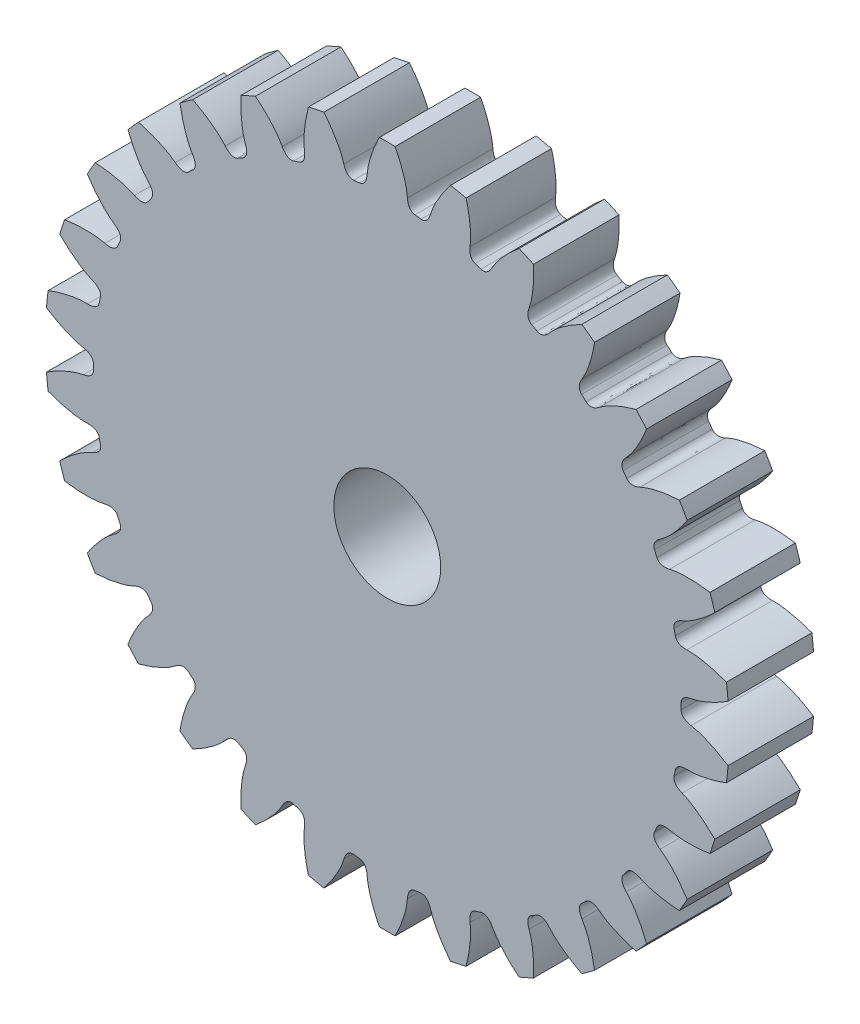
SolidWorks part; units mm, degrees
ref_plane "Спереди" through (0, 0, 0) normal (0, 0, 1) x (1, 0, 0)
ref_plane "Сверху" through (0, 0, 0) normal (0, 1, 0) x (1, 0, 0)
ref_plane "Справа" through (0, 0, 0) normal (1, 0, 0) x (0, 0, -1)
sketch "Sketch1" plane through (0, 0, 0) normal (0, 0, 1) x (1, 0, 0)
  line L0 (-8.8, 0) -> (8.8, 0) construction
  line L1 (0, -8.8) -> (0, 8.8) construction
  arc A0 (0.1843, 7.9979) -> (-0.1843, 7.9979) centre (0, 0) ccw
  arc A1 (-0.6478, 6.8444) -> (-0.7894, 6.8295) centre (0, 0) ccw
  arc A2 (-1.4825, 7.8614) -> (-1.8432, 7.7848) centre (0, 0) ccw
  arc A3 (-2.0566, 6.5602) -> (-2.1921, 6.5162) centre (0, 0) ccw
  arc A4 (-3.0846, 7.3814) -> (-3.4214, 7.2314) centre (0, 0) ccw
  arc A5 (-3.3756, 5.9892) -> (-3.499, 5.918) centre (0, 0) ccw
  arc A6 (-4.5519, 6.5788) -> (-4.8502, 6.3621) centre (0, 0) ccw
  arc A7 (-4.5471, 5.1565) -> (-4.653, 5.0612) centre (0, 0) ccw
  arc A8 (-5.8202, 5.4886) -> (-6.0669, 5.2146) centre (0, 0) ccw
  arc A9 (-5.5198, 4.0984) -> (-5.6036, 3.9832) centre (0, 0) ccw
  arc A10 (-6.8342, 4.1586) -> (-7.0185, 3.8393) centre (0, 0) ccw
  arc A11 (-6.2513, 2.8612) -> (-6.3093, 2.7311) centre (0, 0) ccw
  arc A12 (-7.5495, 2.6468) -> (-7.6634, 2.2962) centre (0, 0) ccw
  arc A13 (-6.7096, 1.499) -> (-6.7392, 1.3597) centre (0, 0) ccw
  arc A14 (-7.9348, 1.0193) -> (-7.9733, 0.6527) centre (0, 0) ccw
  arc A15 (-6.8746, 0.0712) -> (-6.8746, -0.0712) centre (0, 0) ccw
  arc A16 (-7.9733, -0.6527) -> (-7.9348, -1.0193) centre (0, 0) ccw
  arc A17 (-6.7392, -1.3597) -> (-6.7096, -1.499) centre (0, 0) ccw
  arc A18 (-7.6634, -2.2962) -> (-7.5495, -2.6468) centre (0, 0) ccw
  arc A19 (-6.3093, -2.7311) -> (-6.2513, -2.8612) centre (0, 0) ccw
  arc A20 (-7.0185, -3.8393) -> (-6.8342, -4.1586) centre (0, 0) ccw
  arc A21 (-5.6036, -3.9832) -> (-5.5198, -4.0984) centre (0, 0) ccw
  arc A22 (-6.0669, -5.2146) -> (-5.8202, -5.4886) centre (0, 0) ccw
  arc A23 (-4.653, -5.0612) -> (-4.5471, -5.1565) centre (0, 0) ccw
  arc A24 (-4.8502, -6.3621) -> (-4.5519, -6.5788) centre (0, 0) ccw
  arc A25 (-3.499, -5.918) -> (-3.3756, -5.9892) centre (0, 0) ccw
  arc A26 (-3.4214, -7.2314) -> (-3.0846, -7.3814) centre (0, 0) ccw
  arc A27 (-2.1921, -6.5162) -> (-2.0566, -6.5602) centre (0, 0) ccw
  arc A28 (-1.8432, -7.7848) -> (-1.4825, -7.8614) centre (0, 0) ccw
  arc A29 (-0.7894, -6.8295) -> (-0.6478, -6.8444) centre (0, 0) ccw
  arc A30 (-0.1843, -7.9979) -> (0.1843, -7.9979) centre (0, 0) ccw
  arc A31 (0.6478, -6.8444) -> (0.7894, -6.8295) centre (0, 0) ccw
  arc A32 (1.4825, -7.8614) -> (1.8432, -7.7848) centre (0, 0) ccw
  arc A33 (2.0566, -6.5602) -> (2.1921, -6.5162) centre (0, 0) ccw
  arc A34 (3.0846, -7.3814) -> (3.4214, -7.2314) centre (0, 0) ccw
  arc A35 (3.3756, -5.9892) -> (3.499, -5.918) centre (0, 0) ccw
  arc A36 (4.5519, -6.5788) -> (4.8502, -6.3621) centre (0, 0) ccw
  arc A37 (4.5471, -5.1565) -> (4.653, -5.0612) centre (0, 0) ccw
  arc A38 (5.8202, -5.4886) -> (6.0669, -5.2146) centre (0, 0) ccw
  arc A39 (5.5198, -4.0984) -> (5.6036, -3.9832) centre (0, 0) ccw
  arc A40 (6.8342, -4.1586) -> (7.0185, -3.8393) centre (0, 0) ccw
  arc A41 (6.2513, -2.8612) -> (6.3093, -2.7311) centre (0, 0) ccw
  arc A42 (7.5495, -2.6468) -> (7.6634, -2.2962) centre (0, 0) ccw
  arc A43 (6.7096, -1.499) -> (6.7392, -1.3597) centre (0, 0) ccw
  arc A44 (7.9348, -1.0193) -> (7.9733, -0.6527) centre (0, 0) ccw
  arc A45 (6.8746, -0.0712) -> (6.8746, 0.0712) centre (0, 0) ccw
  arc A46 (7.9733, 0.6527) -> (7.9348, 1.0193) centre (0, 0) ccw
  arc A47 (6.7392, 1.3597) -> (6.7096, 1.499) centre (0, 0) ccw
  arc A48 (7.6634, 2.2962) -> (7.5495, 2.6468) centre (0, 0) ccw
  arc A49 (6.3093, 2.7311) -> (6.2513, 2.8612) centre (0, 0) ccw
  arc A50 (7.0185, 3.8393) -> (6.8342, 4.1586) centre (0, 0) ccw
  arc A51 (5.6036, 3.9832) -> (5.5198, 4.0984) centre (0, 0) ccw
  arc A52 (6.0669, 5.2146) -> (5.8202, 5.4886) centre (0, 0) ccw
  arc A53 (4.653, 5.0612) -> (4.5471, 5.1565) centre (0, 0) ccw
  arc A54 (4.8502, 6.3621) -> (4.5519, 6.5788) centre (0, 0) ccw
  arc A55 (3.499, 5.918) -> (3.3756, 5.9892) centre (0, 0) ccw
  arc A56 (3.4214, 7.2314) -> (3.0846, 7.3814) centre (0, 0) ccw
  arc A57 (2.1921, 6.5162) -> (2.0566, 6.5602) centre (0, 0) ccw
  arc A58 (1.8432, 7.7848) -> (1.4825, 7.8614) centre (0, 0) ccw
  arc A59 (0.7894, 6.8295) -> (0.6478, 6.8444) centre (0, 0) ccw
  circle A60 centre (0, 0) radius 7.5 construction
  spline S0 degree 3 poles (0.472, 7.0996) (0.4734, 7.0672) (0.4784, 7.0358) (0.4871, 7.0053) (0.4919, 6.9883) (0.4975, 6.9712) (0.505, 6.9552) (0.5103, 6.9439) (0.5164, 6.9326) (0.5234, 6.9223) (0.5291, 6.9139) (0.5354, 6.9057) (0.5423, 6.8982) (0.5484, 6.8916) (0.5549, 6.8854) (0.5619, 6.8798) (0.5684, 6.8746) (0.5752, 6.8698) (0.5824, 6.8657) (0.5892, 6.8617) (0.5963, 6.8582) (0.6036, 6.8552) (0.6107, 6.8524) (0.618, 6.85) (0.6254, 6.8482) (0.6327, 6.8464) (0.6402, 6.8451) (0.6478, 6.8444) knots 0 0 0 0 1 1 1 2 2 2 3 3 3 4 4 4 5 5 5 6 6 6 7 7 7 8 8 8 9 9 9 9
  spline S1 degree 3 poles (-0.472, 7.0996) (-0.4734, 7.0672) (-0.4784, 7.0358) (-0.4871, 7.0053) (-0.4919, 6.9883) (-0.4975, 6.9712) (-0.505, 6.9552) (-0.5103, 6.9439) (-0.5164, 6.9326) (-0.5234, 6.9223) (-0.5291, 6.9139) (-0.5354, 6.9057) (-0.5423, 6.8982) (-0.5484, 6.8916) (-0.5549, 6.8854) (-0.5619, 6.8798) (-0.5684, 6.8746) (-0.5752, 6.8698) (-0.5824, 6.8657) (-0.5892, 6.8617) (-0.5963, 6.8582) (-0.6036, 6.8552) (-0.6107, 6.8524) (-0.618, 6.85) (-0.6254, 6.8482) (-0.6327, 6.8464) (-0.6402, 6.8451) (-0.6478, 6.8444) knots 0 0 0 0 1 1 1 2 2 2 3 3 3 4 4 4 5 5 5 6 6 6 7 7 7 8 8 8 9 9 9 9
  spline S2 degree 3 poles (0.472, 7.0996) (0.4693, 7.1328) (0.4655, 7.1659) (0.4606, 7.1988) (0.4556, 7.2322) (0.4493, 7.2655) (0.4424, 7.2985) (0.4353, 7.332) (0.4272, 7.3653) (0.4185, 7.3983) (0.4098, 7.4319) (0.4001, 7.4652) (0.3899, 7.4984) (0.3795, 7.5319) (0.3684, 7.5653) (0.3567, 7.5984) (0.3449, 7.632) (0.3324, 7.6653) (0.3194, 7.6985) (0.3062, 7.732) (0.2924, 7.7653) (0.2781, 7.7984) (0.2637, 7.8319) (0.2486, 7.8652) (0.2331, 7.8983) (0.2173, 7.9317) (0.2011, 7.9649) (0.1843, 7.9979) knots 0 0 0 0 1 1 1 2 2 2 3 3 3 4 4 4 5 5 5 6 6 6 7 7 7 8 8 8 9 9 9 9
  spline S3 degree 3 poles (-0.472, 7.0996) (-0.4693, 7.1328) (-0.4655, 7.1659) (-0.4606, 7.1988) (-0.4556, 7.2322) (-0.4493, 7.2655) (-0.4424, 7.2985) (-0.4353, 7.332) (-0.4272, 7.3653) (-0.4185, 7.3983) (-0.4098, 7.4319) (-0.4001, 7.4652) (-0.3899, 7.4984) (-0.3795, 7.5319) (-0.3684, 7.5653) (-0.3567, 7.5984) (-0.3449, 7.632) (-0.3324, 7.6653) (-0.3194, 7.6985) (-0.3062, 7.732) (-0.2924, 7.7653) (-0.2781, 7.7984) (-0.2637, 7.8319) (-0.2486, 7.8652) (-0.2331, 7.8983) (-0.2173, 7.9317) (-0.2011, 7.9649) (-0.1843, 7.9979) knots 0 0 0 0 1 1 1 2 2 2 3 3 3 4 4 4 5 5 5 6 6 6 7 7 7 8 8 8 9 9 9 9
  spline S4 degree 3 poles (-1.0144, 7.0426) (-1.0063, 7.0112) (-0.9949, 6.9815) (-0.98, 6.9535) (-0.9718, 6.9379) (-0.9628, 6.9223) (-0.9521, 6.9082) (-0.9445, 6.8982) (-0.9363, 6.8885) (-0.9273, 6.8798) (-0.9199, 6.8728) (-0.9121, 6.8661) (-0.9038, 6.8602) (-0.8965, 6.8551) (-0.8887, 6.8503) (-0.8807, 6.8463) (-0.8734, 6.8426) (-0.8656, 6.8393) (-0.8578, 6.8367) (-0.8503, 6.8343) (-0.8426, 6.8323) (-0.8349, 6.8309) (-0.8274, 6.8296) (-0.8197, 6.8288) (-0.8121, 6.8286) (-0.8045, 6.8283) (-0.797, 6.8287) (-0.7894, 6.8295) knots 0 0 0 0 1 1 1 2 2 2 3 3 3 4 4 4 5 5 5 6 6 6 7 7 7 8 8 8 9 9 9 9
  spline S5 degree 3 poles (-1.9378, 6.8463) (-1.9324, 6.8144) (-1.9308, 6.7826) (-1.9329, 6.7509) (-1.9341, 6.7333) (-1.936, 6.7154) (-1.94, 6.6982) (-1.9429, 6.686) (-1.9464, 6.6738) (-1.9512, 6.6622) (-1.955, 6.6528) (-1.9595, 6.6435) (-1.9647, 6.6347) (-1.9692, 6.627) (-1.9744, 6.6196) (-1.98, 6.6126) (-1.9853, 6.6062) (-1.991, 6.6001) (-1.9971, 6.5946) (-2.0029, 6.5893) (-2.0092, 6.5843) (-2.0157, 6.5799) (-2.022, 6.5757) (-2.0287, 6.5718) (-2.0356, 6.5685) (-2.0424, 6.5652) (-2.0494, 6.5625) (-2.0566, 6.5602) knots 0 0 0 0 1 1 1 2 2 2 3 3 3 4 4 4 5 5 5 6 6 6 7 7 7 8 8 8 9 9 9 9
  spline S6 degree 3 poles (-1.0144, 7.0426) (-1.024, 7.0745) (-1.0346, 7.1061) (-1.0462, 7.1373) (-1.058, 7.1689) (-1.0711, 7.2001) (-1.0848, 7.231) (-1.0986, 7.2622) (-1.1134, 7.2931) (-1.1288, 7.3237) (-1.1444, 7.3547) (-1.1608, 7.3853) (-1.1776, 7.4156) (-1.1948, 7.4462) (-1.2126, 7.4765) (-1.2309, 7.5065) (-1.2494, 7.5369) (-1.2686, 7.5669) (-1.2882, 7.5966) (-1.308, 7.6267) (-1.3285, 7.6564) (-1.3493, 7.6858) (-1.3705, 7.7156) (-1.3921, 7.745) (-1.4142, 7.7741) (-1.4365, 7.8036) (-1.4593, 7.8327) (-1.4825, 7.8614) knots 0 0 0 0 1 1 1 2 2 2 3 3 3 4 4 4 5 5 5 6 6 6 7 7 7 8 8 8 9 9 9 9
  spline S7 degree 3 poles (-1.9378, 6.8463) (-1.942, 6.8794) (-1.9452, 6.9126) (-1.9473, 6.9458) (-1.9494, 6.9794) (-1.9501, 7.0133) (-1.9501, 7.047) (-1.9502, 7.0812) (-1.9492, 7.1155) (-1.9476, 7.1497) (-1.946, 7.1843) (-1.9435, 7.2189) (-1.9403, 7.2534) (-1.9372, 7.2884) (-1.9332, 7.3234) (-1.9287, 7.3582) (-1.9242, 7.3935) (-1.9189, 7.4287) (-1.913, 7.4638) (-1.9071, 7.4994) (-1.9005, 7.5349) (-1.8934, 7.5702) (-1.8862, 7.606) (-1.8784, 7.6417) (-1.8701, 7.6772) (-1.8617, 7.7132) (-1.8527, 7.7491) (-1.8432, 7.7848) knots 0 0 0 0 1 1 1 2 2 2 3 3 3 4 4 4 5 5 5 6 6 6 7 7 7 8 8 8 9 9 9 9
  spline S8 degree 3 poles (-2.4565, 6.6778) (-2.4421, 6.6488) (-2.4247, 6.6221) (-2.4043, 6.5977) (-2.393, 6.5842) (-2.381, 6.5708) (-2.3676, 6.5593) (-2.3581, 6.5511) (-2.3481, 6.5433) (-2.3374, 6.5367) (-2.3288, 6.5313) (-2.3197, 6.5264) (-2.3103, 6.5224) (-2.3021, 6.5189) (-2.2936, 6.5158) (-2.2849, 6.5136) (-2.2769, 6.5115) (-2.2687, 6.5099) (-2.2605, 6.509) (-2.2527, 6.5081) (-2.2447, 6.5078) (-2.2369, 6.5081) (-2.2292, 6.5083) (-2.2216, 6.5091) (-2.214, 6.5105) (-2.2066, 6.5119) (-2.1993, 6.5137) (-2.1921, 6.5162) knots 0 0 0 0 1 1 1 2 2 2 3 3 3 4 4 4 5 5 5 6 6 6 7 7 7 8 8 8 9 9 9 9
  spline S9 degree 3 poles (-3.3188, 6.2938) (-3.3069, 6.2637) (-3.2987, 6.2329) (-3.2943, 6.2015) (-3.2918, 6.184) (-3.2899, 6.1661) (-3.2903, 6.1485) (-3.2905, 6.136) (-3.2915, 6.1233) (-3.2937, 6.1109) (-3.2955, 6.1009) (-3.2979, 6.0909) (-3.3012, 6.0813) (-3.304, 6.0728) (-3.3075, 6.0644) (-3.3116, 6.0564) (-3.3154, 6.0491) (-3.3197, 6.0419) (-3.3245, 6.0352) (-3.3291, 6.0288) (-3.3342, 6.0227) (-3.3397, 6.0171) (-3.345, 6.0116) (-3.3507, 6.0064) (-3.3568, 6.0017) (-3.3627, 5.9971) (-3.369, 5.993) (-3.3756, 5.9892) knots 0 0 0 0 1 1 1 2 2 2 3 3 3 4 4 4 5 5 5 6 6 6 7 7 7 8 8 8 9 9 9 9
  spline S10 degree 3 poles (-2.4565, 6.6778) (-2.4725, 6.707) (-2.4894, 6.7357) (-2.5073, 6.7638) (-2.5254, 6.7923) (-2.5447, 6.8201) (-2.5645, 6.8474) (-2.5845, 6.8751) (-2.6054, 6.9023) (-2.6268, 6.929) (-2.6485, 6.956) (-2.6709, 6.9826) (-2.6937, 7.0087) (-2.7168, 7.0351) (-2.7405, 7.0611) (-2.7647, 7.0866) (-2.7891, 7.1125) (-2.8141, 7.1378) (-2.8395, 7.1628) (-2.8651, 7.1881) (-2.8913, 7.2129) (-2.9178, 7.2373) (-2.9447, 7.2621) (-2.972, 7.2863) (-2.9996, 7.3102) (-3.0276, 7.3344) (-3.0559, 7.3581) (-3.0846, 7.3814) knots 0 0 0 0 1 1 1 2 2 2 3 3 3 4 4 4 5 5 5 6 6 6 7 7 7 8 8 8 9 9 9 9
  spline S11 degree 3 poles (-3.3188, 6.2938) (-3.3299, 6.3253) (-3.3399, 6.3571) (-3.3488, 6.3891) (-3.3579, 6.4216) (-3.3656, 6.4546) (-3.3727, 6.4876) (-3.3798, 6.521) (-3.386, 6.5547) (-3.3915, 6.5885) (-3.3971, 6.6227) (-3.4019, 6.6571) (-3.406, 6.6915) (-3.4102, 6.7264) (-3.4136, 6.7614) (-3.4164, 6.7964) (-3.4193, 6.8319) (-3.4214, 6.8674) (-3.423, 6.903) (-3.4246, 6.939) (-3.4256, 6.9751) (-3.426, 7.0111) (-3.4264, 7.0476) (-3.4262, 7.0841) (-3.4254, 7.1206) (-3.4247, 7.1576) (-3.4233, 7.1945) (-3.4214, 7.2314) knots 0 0 0 0 1 1 1 2 2 2 3 3 3 4 4 4 5 5 5 6 6 6 7 7 7 8 8 8 9 9 9 9
  spline S12 degree 3 poles (-3.7912, 6.0211) (-3.771, 5.9957) (-3.7485, 5.9733) (-3.7235, 5.9537) (-3.7096, 5.9428) (-3.6951, 5.9322) (-3.6796, 5.9237) (-3.6686, 5.9177) (-3.6572, 5.9121) (-3.6454, 5.9079) (-3.6358, 5.9044) (-3.6259, 5.9015) (-3.6159, 5.8995) (-3.6072, 5.8978) (-3.5982, 5.8966) (-3.5892, 5.8962) (-3.581, 5.8958) (-3.5726, 5.8959) (-3.5644, 5.8968) (-3.5566, 5.8975) (-3.5487, 5.8989) (-3.5411, 5.9008) (-3.5337, 5.9026) (-3.5263, 5.905) (-3.5193, 5.9079) (-3.5123, 5.9108) (-3.5055, 5.9141) (-3.499, 5.918) knots 0 0 0 0 1 1 1 2 2 2 3 3 3 4 4 4 5 5 5 6 6 6 7 7 7 8 8 8 9 9 9 9
  spline S13 degree 3 poles (-4.5549, 5.4663) (-4.537, 5.4393) (-4.5226, 5.4109) (-4.5117, 5.3811) (-4.5056, 5.3645) (-4.5, 5.3474) (-4.4967, 5.33) (-4.4944, 5.3177) (-4.4926, 5.3051) (-4.4922, 5.2926) (-4.4919, 5.2824) (-4.4922, 5.2721) (-4.4934, 5.262) (-4.4944, 5.2531) (-4.4961, 5.2442) (-4.4985, 5.2356) (-4.5006, 5.2276) (-4.5034, 5.2197) (-4.5067, 5.2121) (-4.5098, 5.2049) (-4.5135, 5.1979) (-4.5177, 5.1912) (-4.5218, 5.1847) (-4.5263, 5.1785) (-4.5312, 5.1727) (-4.5361, 5.1669) (-4.5414, 5.1615) (-4.5471, 5.1565) knots 0 0 0 0 1 1 1 2 2 2 3 3 3 4 4 4 5 5 5 6 6 6 7 7 7 8 8 8 9 9 9 9
  spline S14 degree 3 poles (-3.7912, 6.0211) (-3.8129, 6.0464) (-3.8354, 6.071) (-3.8587, 6.0947) (-3.8824, 6.1188) (-3.907, 6.142) (-3.9321, 6.1646) (-3.9574, 6.1875) (-3.9836, 6.2097) (-4.01, 6.2314) (-4.0369, 6.2534) (-4.0643, 6.2747) (-4.092, 6.2955) (-4.1201, 6.3165) (-4.1487, 6.337) (-4.1776, 6.3569) (-4.2069, 6.3771) (-4.2366, 6.3968) (-4.2666, 6.4159) (-4.297, 6.4353) (-4.3278, 6.4542) (-4.3588, 6.4725) (-4.3902, 6.4911) (-4.4219, 6.5092) (-4.4539, 6.5268) (-4.4863, 6.5446) (-4.519, 6.562) (-4.5519, 6.5788) knots 0 0 0 0 1 1 1 2 2 2 3 3 3 4 4 4 5 5 5 6 6 6 7 7 7 8 8 8 9 9 9 9
  spline S15 degree 3 poles (-4.5549, 5.4663) (-4.5722, 5.4947) (-4.5886, 5.5237) (-4.604, 5.5533) (-4.6196, 5.5832) (-4.634, 5.6138) (-4.6478, 5.6446) (-4.6618, 5.6758) (-4.6748, 5.7075) (-4.6873, 5.7394) (-4.6998, 5.7717) (-4.7116, 5.8043) (-4.7228, 5.8371) (-4.7342, 5.8704) (-4.7448, 5.9039) (-4.7548, 5.9376) (-4.765, 5.9717) (-4.7745, 6.006) (-4.7834, 6.0404) (-4.7925, 6.0753) (-4.8009, 6.1104) (-4.8088, 6.1456) (-4.8168, 6.1812) (-4.8242, 6.217) (-4.831, 6.2528) (-4.838, 6.2891) (-4.8443, 6.3255) (-4.8502, 6.3621) knots 0 0 0 0 1 1 1 2 2 2 3 3 3 4 4 4 5 5 5 6 6 6 7 7 7 8 8 8 9 9 9 9
  spline S16 degree 3 poles (-4.9602, 5.1013) (-4.9352, 5.0807) (-4.9085, 5.0634) (-4.88, 5.0494) (-4.8641, 5.0417) (-4.8477, 5.0343) (-4.8308, 5.0292) (-4.8188, 5.0256) (-4.8065, 5.0226) (-4.794, 5.0209) (-4.784, 5.0195) (-4.7737, 5.0187) (-4.7635, 5.0188) (-4.7546, 5.0189) (-4.7455, 5.0196) (-4.7367, 5.0211) (-4.7285, 5.0224) (-4.7204, 5.0243) (-4.7125, 5.0268) (-4.705, 5.0292) (-4.6976, 5.0321) (-4.6906, 5.0356) (-4.6837, 5.0389) (-4.677, 5.0428) (-4.6707, 5.0471) (-4.6645, 5.0514) (-4.6586, 5.056) (-4.653, 5.0612) knots 0 0 0 0 1 1 1 2 2 2 3 3 3 4 4 4 5 5 5 6 6 6 7 7 7 8 8 8 9 9 9 9
  spline S17 degree 3 poles (-5.5918, 4.3998) (-5.5687, 4.3771) (-5.5487, 4.3523) (-5.5319, 4.3255) (-5.5225, 4.3105) (-5.5135, 4.2949) (-5.5066, 4.2786) (-5.5018, 4.2671) (-5.4975, 4.2551) (-5.4945, 4.243) (-5.492, 4.2331) (-5.4902, 4.2229) (-5.4892, 4.2128) (-5.4884, 4.2039) (-5.4882, 4.1948) (-5.4887, 4.1859) (-5.4892, 4.1776) (-5.4902, 4.1693) (-5.4919, 4.1612) (-5.4935, 4.1535) (-5.4956, 4.1459) (-5.4983, 4.1385) (-5.5009, 4.1313) (-5.5041, 4.1243) (-5.5077, 4.1175) (-5.5113, 4.1109) (-5.5153, 4.1045) (-5.5198, 4.0984) knots 0 0 0 0 1 1 1 2 2 2 3 3 3 4 4 4 5 5 5 6 6 6 7 7 7 8 8 8 9 9 9 9
  spline S18 degree 3 poles (-4.9602, 5.1013) (-4.9867, 5.1215) (-5.0138, 5.1409) (-5.0416, 5.1593) (-5.0697, 5.1779) (-5.0986, 5.1954) (-5.1278, 5.2124) (-5.1574, 5.2295) (-5.1876, 5.2458) (-5.218, 5.2615) (-5.2488, 5.2774) (-5.28, 5.2925) (-5.3115, 5.3071) (-5.3434, 5.3219) (-5.3756, 5.3359) (-5.408, 5.3494) (-5.4409, 5.3631) (-5.474, 5.3761) (-5.5074, 5.3886) (-5.5411, 5.4013) (-5.5751, 5.4133) (-5.6093, 5.4249) (-5.6438, 5.4365) (-5.6787, 5.4476) (-5.7136, 5.4582) (-5.749, 5.4689) (-5.7845, 5.479) (-5.8202, 5.4886) knots 0 0 0 0 1 1 1 2 2 2 3 3 3 4 4 4 5 5 5 6 6 6 7 7 7 8 8 8 9 9 9 9
  spline S19 degree 3 poles (-5.5918, 4.3998) (-5.6147, 4.4241) (-5.6368, 4.449) (-5.658, 4.4747) (-5.6795, 4.5007) (-5.6999, 4.5276) (-5.7198, 4.5549) (-5.74, 4.5825) (-5.7593, 4.6108) (-5.7781, 4.6394) (-5.7971, 4.6684) (-5.8155, 4.6979) (-5.8332, 4.7277) (-5.8512, 4.7578) (-5.8686, 4.7884) (-5.8854, 4.8192) (-5.9025, 4.8505) (-5.9189, 4.8821) (-5.9348, 4.9139) (-5.9509, 4.9462) (-5.9664, 4.9787) (-5.9815, 5.0115) (-5.9967, 5.0447) (-6.0113, 5.0781) (-6.0255, 5.1118) (-6.0398, 5.1458) (-6.0536, 5.1801) (-6.0669, 5.2146) knots 0 0 0 0 1 1 1 2 2 2 3 3 3 4 4 4 5 5 5 6 6 6 7 7 7 8 8 8 9 9 9 9
  spline S20 degree 3 poles (-5.9124, 3.9585) (-5.8837, 3.9436) (-5.854, 3.9322) (-5.8232, 3.9245) (-5.8061, 3.9202) (-5.7885, 3.9164) (-5.7709, 3.9149) (-5.7584, 3.9139) (-5.7457, 3.9135) (-5.7332, 3.9144) (-5.723, 3.9151) (-5.7128, 3.9165) (-5.7029, 3.9187) (-5.6942, 3.9207) (-5.6855, 3.9233) (-5.6771, 3.9265) (-5.6694, 3.9295) (-5.6618, 3.9331) (-5.6547, 3.9372) (-5.6478, 3.9411) (-5.6412, 3.9455) (-5.635, 3.9503) (-5.629, 3.955) (-5.6233, 3.9602) (-5.618, 3.9657) (-5.6128, 3.9712) (-5.608, 3.977) (-5.6036, 3.9832) knots 0 0 0 0 1 1 1 2 2 2 3 3 3 4 4 4 5 5 5 6 6 6 7 7 7 8 8 8 9 9 9 9
  spline S21 degree 3 poles (-6.3844, 3.141) (-6.3571, 3.1237) (-6.3324, 3.1036) (-6.3103, 3.0808) (-6.298, 3.0681) (-6.2859, 3.0548) (-6.2759, 3.0402) (-6.2687, 3.03) (-6.262, 3.0191) (-6.2566, 3.0079) (-6.2521, 2.9987) (-6.2482, 2.9892) (-6.2452, 2.9795) (-6.2425, 2.9709) (-6.2404, 2.9621) (-6.239, 2.9533) (-6.2378, 2.9451) (-6.2371, 2.9367) (-6.237, 2.9285) (-6.237, 2.9206) (-6.2375, 2.9127) (-6.2386, 2.9049) (-6.2397, 2.8973) (-6.2413, 2.8898) (-6.2434, 2.8825) (-6.2455, 2.8752) (-6.2482, 2.8681) (-6.2513, 2.8612) knots 0 0 0 0 1 1 1 2 2 2 3 3 3 4 4 4 5 5 5 6 6 6 7 7 7 8 8 8 9 9 9 9
  spline S22 degree 3 poles (-5.9124, 3.9585) (-5.9426, 3.9728) (-5.9731, 3.9861) (-6.0041, 3.9983) (-6.0355, 4.0107) (-6.0674, 4.0218) (-6.0995, 4.0323) (-6.132, 4.043) (-6.1649, 4.0526) (-6.1979, 4.0616) (-6.2313, 4.0708) (-6.265, 4.0791) (-6.2988, 4.0868) (-6.3331, 4.0946) (-6.3675, 4.1017) (-6.4021, 4.1081) (-6.437, 4.1147) (-6.4722, 4.1205) (-6.5074, 4.1258) (-6.543, 4.1312) (-6.5788, 4.1359) (-6.6146, 4.1401) (-6.6508, 4.1443) (-6.6872, 4.1479) (-6.7236, 4.151) (-6.7604, 4.1541) (-6.7973, 4.1566) (-6.8342, 4.1586) knots 0 0 0 0 1 1 1 2 2 2 3 3 3 4 4 4 5 5 5 6 6 6 7 7 7 8 8 8 9 9 9 9
  spline S23 degree 3 poles (-6.3844, 3.141) (-6.4119, 3.16) (-6.4386, 3.1798) (-6.4647, 3.2005) (-6.4911, 3.2215) (-6.5167, 3.2436) (-6.5418, 3.2662) (-6.5673, 3.289) (-6.5921, 3.3126) (-6.6164, 3.3367) (-6.6411, 3.3611) (-6.6651, 3.3861) (-6.6887, 3.4115) (-6.7126, 3.4373) (-6.7359, 3.4636) (-6.7588, 3.4903) (-6.7819, 3.5173) (-6.8046, 3.5448) (-6.8268, 3.5726) (-6.8492, 3.6008) (-6.8712, 3.6294) (-6.8927, 3.6583) (-6.9145, 3.6876) (-6.9358, 3.7173) (-6.9566, 3.7473) (-6.9777, 3.7776) (-6.9984, 3.8083) (-7.0185, 3.8393) knots 0 0 0 0 1 1 1 2 2 2 3 3 3 4 4 4 5 5 5 6 6 6 7 7 7 8 8 8 9 9 9 9
  spline S24 degree 3 poles (-6.6063, 2.6428) (-6.575, 2.6341) (-6.5436, 2.6292) (-6.5119, 2.628) (-6.4942, 2.6274) (-6.4762, 2.6273) (-6.4587, 2.6296) (-6.4463, 2.6311) (-6.4338, 2.6334) (-6.4217, 2.6369) (-6.412, 2.6397) (-6.4023, 2.6432) (-6.393, 2.6474) (-6.3849, 2.6512) (-6.3769, 2.6555) (-6.3694, 2.6604) (-6.3625, 2.6649) (-6.3558, 2.67) (-6.3497, 2.6755) (-6.3438, 2.6807) (-6.3382, 2.6864) (-6.3332, 2.6924) (-6.3283, 2.6983) (-6.3237, 2.7045) (-6.3197, 2.711) (-6.3158, 2.7174) (-6.3123, 2.7241) (-6.3093, 2.7311) knots 0 0 0 0 1 1 1 2 2 2 3 3 3 4 4 4 5 5 5 6 6 6 7 7 7 8 8 8 9 9 9 9
  spline S25 degree 3 poles (-6.898, 1.745) (-6.8676, 1.7337) (-6.8393, 1.7192) (-6.8129, 1.7015) (-6.7983, 1.6916) (-6.7837, 1.6811) (-6.7708, 1.669) (-6.7617, 1.6604) (-6.7529, 1.6512) (-6.7452, 1.6413) (-6.739, 1.6333) (-6.7331, 1.6248) (-6.7282, 1.6159) (-6.7238, 1.6081) (-6.7199, 1.5999) (-6.7167, 1.5915) (-6.7138, 1.5838) (-6.7114, 1.5758) (-6.7096, 1.5677) (-6.7079, 1.5601) (-6.7068, 1.5522) (-6.7062, 1.5443) (-6.7057, 1.5367) (-6.7057, 1.529) (-6.7063, 1.5214) (-6.7068, 1.5139) (-6.7079, 1.5064) (-6.7096, 1.499) knots 0 0 0 0 1 1 1 2 2 2 3 3 3 4 4 4 5 5 5 6 6 6 7 7 7 8 8 8 9 9 9 9
  spline S26 degree 3 poles (-6.6063, 2.6428) (-6.6387, 2.6505) (-6.6714, 2.6571) (-6.7042, 2.6626) (-6.7375, 2.6682) (-6.771, 2.6725) (-6.8046, 2.6761) (-6.8386, 2.6797) (-6.8728, 2.6823) (-6.9069, 2.6843) (-6.9415, 2.6863) (-6.9762, 2.6874) (-7.0109, 2.6879) (-7.046, 2.6884) (-7.0812, 2.6881) (-7.1163, 2.6873) (-7.1519, 2.6864) (-7.1874, 2.6849) (-7.223, 2.6827) (-7.259, 2.6806) (-7.2949, 2.6777) (-7.3308, 2.6744) (-7.3671, 2.671) (-7.4035, 2.6669) (-7.4397, 2.6624) (-7.4763, 2.6577) (-7.5129, 2.6525) (-7.5495, 2.6468) knots 0 0 0 0 1 1 1 2 2 2 3 3 3 4 4 4 5 5 5 6 6 6 7 7 7 8 8 8 9 9 9 9
  spline S27 degree 3 poles (-6.898, 1.745) (-6.9288, 1.7579) (-6.959, 1.7717) (-6.9888, 1.7865) (-7.0191, 1.8015) (-7.0487, 1.8178) (-7.078, 1.8347) (-7.1076, 1.8517) (-7.1368, 1.8697) (-7.1656, 1.8882) (-7.1948, 1.9069) (-7.2235, 1.9264) (-7.2518, 1.9463) (-7.2806, 1.9666) (-7.3088, 1.9874) (-7.3368, 2.0088) (-7.365, 2.0304) (-7.3929, 2.0526) (-7.4204, 2.0752) (-7.4482, 2.0981) (-7.4756, 2.1215) (-7.5027, 2.1453) (-7.5301, 2.1695) (-7.5571, 2.1941) (-7.5837, 2.219) (-7.6107, 2.2443) (-7.6372, 2.27) (-7.6634, 2.2962) knots 0 0 0 0 1 1 1 2 2 2 3 3 3 4 4 4 5 5 5 6 6 6 7 7 7 8 8 8 9 9 9 9
  spline S28 degree 3 poles (-7.0114, 1.2115) (-6.979, 1.2095) (-6.9472, 1.2112) (-6.916, 1.2167) (-6.8986, 1.2197) (-6.881, 1.2234) (-6.8643, 1.2293) (-6.8525, 1.2334) (-6.8407, 1.2382) (-6.8297, 1.2441) (-6.8207, 1.2489) (-6.8119, 1.2543) (-6.8037, 1.2604) (-6.7966, 1.2657) (-6.7897, 1.2716) (-6.7834, 1.278) (-6.7776, 1.2839) (-6.7721, 1.2902) (-6.7672, 1.2968) (-6.7625, 1.3032) (-6.7583, 1.3099) (-6.7546, 1.3168) (-6.751, 1.3236) (-6.7479, 1.3306) (-6.7453, 1.3378) (-6.7427, 1.3449) (-6.7407, 1.3522) (-6.7392, 1.3597) knots 0 0 0 0 1 1 1 2 2 2 3 3 3 4 4 4 5 5 5 6 6 6 7 7 7 8 8 8 9 9 9 9
  spline S29 degree 3 poles (-7.11, 0.2727) (-7.078, 0.268) (-7.0472, 0.2597) (-7.0178, 0.2478) (-7.0014, 0.2412) (-6.985, 0.2339) (-6.9699, 0.2248) (-6.9592, 0.2183) (-6.9486, 0.2111) (-6.9391, 0.2031) (-6.9313, 0.1965) (-6.9238, 0.1894) (-6.9171, 0.1817) (-6.9112, 0.175) (-6.9057, 0.1678) (-6.9008, 0.1603) (-6.8964, 0.1533) (-6.8923, 0.146) (-6.8889, 0.1385) (-6.8857, 0.1313) (-6.8829, 0.1238) (-6.8808, 0.1163) (-6.8787, 0.109) (-6.8771, 0.1014) (-6.876, 0.0938) (-6.875, 0.0864) (-6.8746, 0.0788) (-6.8746, 0.0712) knots 0 0 0 0 1 1 1 2 2 2 3 3 3 4 4 4 5 5 5 6 6 6 7 7 7 8 8 8 9 9 9 9
  spline S30 degree 3 poles (-7.0114, 1.2115) (-7.0447, 1.2123) (-7.078, 1.212) (-7.1113, 1.2106) (-7.145, 1.2091) (-7.1787, 1.2063) (-7.2123, 1.2028) (-7.2463, 1.1993) (-7.2802, 1.1948) (-7.3141, 1.1896) (-7.3483, 1.1844) (-7.3825, 1.1782) (-7.4165, 1.1715) (-7.451, 1.1647) (-7.4853, 1.1571) (-7.5195, 1.149) (-7.5541, 1.1408) (-7.5886, 1.1318) (-7.6229, 1.1224) (-7.6577, 1.1128) (-7.6922, 1.1025) (-7.7266, 1.0918) (-7.7615, 1.0809) (-7.7962, 1.0694) (-7.8306, 1.0574) (-7.8655, 1.0452) (-7.9003, 1.0326) (-7.9348, 1.0193) knots 0 0 0 0 1 1 1 2 2 2 3 3 3 4 4 4 5 5 5 6 6 6 7 7 7 8 8 8 9 9 9 9
  spline S31 degree 3 poles (-7.11, 0.2727) (-7.1428, 0.2789) (-7.1753, 0.2861) (-7.2076, 0.2944) (-7.2402, 0.3028) (-7.2726, 0.3126) (-7.3047, 0.323) (-7.3373, 0.3335) (-7.3696, 0.345) (-7.4016, 0.3571) (-7.434, 0.3693) (-7.4661, 0.3824) (-7.498, 0.3961) (-7.5303, 0.4099) (-7.5623, 0.4244) (-7.5941, 0.4395) (-7.6262, 0.4547) (-7.6581, 0.4707) (-7.6897, 0.4871) (-7.7217, 0.5037) (-7.7534, 0.5209) (-7.7848, 0.5386) (-7.8166, 0.5565) (-7.8481, 0.5749) (-7.8794, 0.5938) (-7.911, 0.6129) (-7.9423, 0.6326) (-7.9733, 0.6527) knots 0 0 0 0 1 1 1 2 2 2 3 3 3 4 4 4 5 5 5 6 6 6 7 7 7 8 8 8 9 9 9 9
  spline S32 degree 3 poles (-7.11, -0.2727) (-7.078, -0.268) (-7.0472, -0.2597) (-7.0178, -0.2478) (-7.0014, -0.2412) (-6.985, -0.2339) (-6.9699, -0.2248) (-6.9592, -0.2183) (-6.9486, -0.2111) (-6.9391, -0.2031) (-6.9313, -0.1965) (-6.9238, -0.1894) (-6.9171, -0.1817) (-6.9112, -0.175) (-6.9057, -0.1678) (-6.9008, -0.1603) (-6.8964, -0.1533) (-6.8923, -0.146) (-6.8889, -0.1385) (-6.8857, -0.1313) (-6.8829, -0.1238) (-6.8808, -0.1163) (-6.8787, -0.109) (-6.8771, -0.1014) (-6.876, -0.0938) (-6.875, -0.0864) (-6.8746, -0.0788) (-6.8746, -0.0712) knots 0 0 0 0 1 1 1 2 2 2 3 3 3 4 4 4 5 5 5 6 6 6 7 7 7 8 8 8 9 9 9 9
  spline S33 degree 3 poles (-7.0114, -1.2115) (-6.979, -1.2095) (-6.9472, -1.2112) (-6.916, -1.2167) (-6.8986, -1.2197) (-6.881, -1.2234) (-6.8643, -1.2293) (-6.8525, -1.2334) (-6.8407, -1.2382) (-6.8297, -1.2441) (-6.8207, -1.2489) (-6.8119, -1.2543) (-6.8037, -1.2604) (-6.7966, -1.2657) (-6.7897, -1.2716) (-6.7834, -1.278) (-6.7776, -1.2839) (-6.7721, -1.2902) (-6.7672, -1.2968) (-6.7625, -1.3032) (-6.7583, -1.3099) (-6.7546, -1.3168) (-6.751, -1.3236) (-6.7479, -1.3306) (-6.7453, -1.3378) (-6.7427, -1.3449) (-6.7407, -1.3522) (-6.7392, -1.3597) knots 0 0 0 0 1 1 1 2 2 2 3 3 3 4 4 4 5 5 5 6 6 6 7 7 7 8 8 8 9 9 9 9
  spline S34 degree 3 poles (-7.11, -0.2727) (-7.1428, -0.2789) (-7.1753, -0.2861) (-7.2076, -0.2944) (-7.2402, -0.3028) (-7.2726, -0.3126) (-7.3047, -0.323) (-7.3373, -0.3335) (-7.3696, -0.345) (-7.4016, -0.3571) (-7.434, -0.3693) (-7.4661, -0.3824) (-7.498, -0.3961) (-7.5303, -0.4099) (-7.5623, -0.4244) (-7.5941, -0.4395) (-7.6262, -0.4547) (-7.6581, -0.4707) (-7.6897, -0.4871) (-7.7217, -0.5037) (-7.7534, -0.5209) (-7.7848, -0.5386) (-7.8166, -0.5565) (-7.8481, -0.5749) (-7.8794, -0.5938) (-7.911, -0.6129) (-7.9423, -0.6326) (-7.9733, -0.6527) knots 0 0 0 0 1 1 1 2 2 2 3 3 3 4 4 4 5 5 5 6 6 6 7 7 7 8 8 8 9 9 9 9
  spline S35 degree 3 poles (-7.0114, -1.2115) (-7.0447, -1.2123) (-7.078, -1.212) (-7.1113, -1.2106) (-7.145, -1.2091) (-7.1787, -1.2063) (-7.2123, -1.2028) (-7.2463, -1.1993) (-7.2802, -1.1948) (-7.3141, -1.1896) (-7.3483, -1.1844) (-7.3825, -1.1782) (-7.4165, -1.1715) (-7.451, -1.1647) (-7.4853, -1.1571) (-7.5195, -1.149) (-7.5541, -1.1408) (-7.5886, -1.1318) (-7.6229, -1.1224) (-7.6577, -1.1128) (-7.6922, -1.1025) (-7.7266, -1.0918) (-7.7615, -1.0809) (-7.7962, -1.0694) (-7.8306, -1.0574) (-7.8655, -1.0452) (-7.9003, -1.0326) (-7.9348, -1.0193) knots 0 0 0 0 1 1 1 2 2 2 3 3 3 4 4 4 5 5 5 6 6 6 7 7 7 8 8 8 9 9 9 9
  spline S36 degree 3 poles (-6.898, -1.745) (-6.8676, -1.7337) (-6.8393, -1.7192) (-6.8129, -1.7015) (-6.7983, -1.6916) (-6.7837, -1.6811) (-6.7708, -1.669) (-6.7617, -1.6604) (-6.7529, -1.6512) (-6.7452, -1.6413) (-6.739, -1.6333) (-6.7331, -1.6248) (-6.7282, -1.6159) (-6.7238, -1.6081) (-6.7199, -1.5999) (-6.7167, -1.5915) (-6.7138, -1.5838) (-6.7114, -1.5758) (-6.7096, -1.5677) (-6.7079, -1.5601) (-6.7068, -1.5522) (-6.7062, -1.5443) (-6.7057, -1.5367) (-6.7057, -1.529) (-6.7063, -1.5214) (-6.7068, -1.5139) (-6.7079, -1.5064) (-6.7096, -1.499) knots 0 0 0 0 1 1 1 2 2 2 3 3 3 4 4 4 5 5 5 6 6 6 7 7 7 8 8 8 9 9 9 9
  spline S37 degree 3 poles (-6.6063, -2.6428) (-6.575, -2.6341) (-6.5436, -2.6292) (-6.5119, -2.628) (-6.4942, -2.6274) (-6.4762, -2.6273) (-6.4587, -2.6296) (-6.4463, -2.6311) (-6.4338, -2.6334) (-6.4217, -2.6369) (-6.412, -2.6397) (-6.4023, -2.6432) (-6.393, -2.6474) (-6.3849, -2.6512) (-6.3769, -2.6555) (-6.3694, -2.6604) (-6.3625, -2.6649) (-6.3558, -2.67) (-6.3497, -2.6755) (-6.3438, -2.6807) (-6.3382, -2.6864) (-6.3332, -2.6924) (-6.3283, -2.6983) (-6.3237, -2.7045) (-6.3197, -2.711) (-6.3158, -2.7174) (-6.3123, -2.7241) (-6.3093, -2.7311) knots 0 0 0 0 1 1 1 2 2 2 3 3 3 4 4 4 5 5 5 6 6 6 7 7 7 8 8 8 9 9 9 9
  spline S38 degree 3 poles (-6.898, -1.745) (-6.9288, -1.7579) (-6.959, -1.7717) (-6.9888, -1.7865) (-7.0191, -1.8015) (-7.0487, -1.8178) (-7.078, -1.8347) (-7.1076, -1.8517) (-7.1368, -1.8697) (-7.1656, -1.8882) (-7.1948, -1.9069) (-7.2235, -1.9264) (-7.2518, -1.9463) (-7.2806, -1.9666) (-7.3088, -1.9874) (-7.3368, -2.0088) (-7.365, -2.0304) (-7.3929, -2.0526) (-7.4204, -2.0752) (-7.4482, -2.0981) (-7.4756, -2.1215) (-7.5027, -2.1453) (-7.5301, -2.1695) (-7.5571, -2.1941) (-7.5837, -2.219) (-7.6107, -2.2443) (-7.6372, -2.27) (-7.6634, -2.2962) knots 0 0 0 0 1 1 1 2 2 2 3 3 3 4 4 4 5 5 5 6 6 6 7 7 7 8 8 8 9 9 9 9
  spline S39 degree 3 poles (-6.6063, -2.6428) (-6.6387, -2.6505) (-6.6714, -2.6571) (-6.7042, -2.6626) (-6.7375, -2.6682) (-6.771, -2.6725) (-6.8046, -2.6761) (-6.8386, -2.6797) (-6.8728, -2.6823) (-6.9069, -2.6843) (-6.9415, -2.6863) (-6.9762, -2.6874) (-7.0109, -2.6879) (-7.046, -2.6884) (-7.0812, -2.6881) (-7.1163, -2.6873) (-7.1519, -2.6864) (-7.1874, -2.6849) (-7.223, -2.6827) (-7.259, -2.6806) (-7.2949, -2.6777) (-7.3308, -2.6744) (-7.3671, -2.671) (-7.4035, -2.6669) (-7.4397, -2.6624) (-7.4763, -2.6577) (-7.5129, -2.6525) (-7.5495, -2.6468) knots 0 0 0 0 1 1 1 2 2 2 3 3 3 4 4 4 5 5 5 6 6 6 7 7 7 8 8 8 9 9 9 9
  spline S40 degree 3 poles (-6.3844, -3.141) (-6.3571, -3.1237) (-6.3324, -3.1036) (-6.3103, -3.0808) (-6.298, -3.0681) (-6.2859, -3.0548) (-6.2759, -3.0402) (-6.2687, -3.03) (-6.262, -3.0191) (-6.2566, -3.0079) (-6.2521, -2.9987) (-6.2482, -2.9892) (-6.2452, -2.9795) (-6.2425, -2.9709) (-6.2404, -2.9621) (-6.239, -2.9533) (-6.2378, -2.9451) (-6.2371, -2.9367) (-6.237, -2.9285) (-6.237, -2.9206) (-6.2375, -2.9127) (-6.2386, -2.9049) (-6.2397, -2.8973) (-6.2413, -2.8898) (-6.2434, -2.8825) (-6.2455, -2.8752) (-6.2482, -2.8681) (-6.2513, -2.8612) knots 0 0 0 0 1 1 1 2 2 2 3 3 3 4 4 4 5 5 5 6 6 6 7 7 7 8 8 8 9 9 9 9
  spline S41 degree 3 poles (-5.9124, -3.9585) (-5.8837, -3.9436) (-5.854, -3.9322) (-5.8232, -3.9245) (-5.8061, -3.9202) (-5.7885, -3.9164) (-5.7709, -3.9149) (-5.7584, -3.9139) (-5.7457, -3.9135) (-5.7332, -3.9144) (-5.723, -3.9151) (-5.7128, -3.9165) (-5.7029, -3.9187) (-5.6942, -3.9207) (-5.6855, -3.9233) (-5.6771, -3.9265) (-5.6694, -3.9295) (-5.6618, -3.9331) (-5.6547, -3.9372) (-5.6478, -3.9411) (-5.6412, -3.9455) (-5.635, -3.9503) (-5.629, -3.955) (-5.6233, -3.9602) (-5.618, -3.9657) (-5.6128, -3.9712) (-5.608, -3.977) (-5.6036, -3.9832) knots 0 0 0 0 1 1 1 2 2 2 3 3 3 4 4 4 5 5 5 6 6 6 7 7 7 8 8 8 9 9 9 9
  spline S42 degree 3 poles (-6.3844, -3.141) (-6.4119, -3.16) (-6.4386, -3.1798) (-6.4647, -3.2005) (-6.4911, -3.2215) (-6.5167, -3.2436) (-6.5418, -3.2662) (-6.5673, -3.289) (-6.5921, -3.3126) (-6.6164, -3.3367) (-6.6411, -3.3611) (-6.6651, -3.3861) (-6.6887, -3.4115) (-6.7126, -3.4373) (-6.7359, -3.4636) (-6.7588, -3.4903) (-6.7819, -3.5173) (-6.8046, -3.5448) (-6.8268, -3.5726) (-6.8492, -3.6008) (-6.8712, -3.6294) (-6.8927, -3.6583) (-6.9145, -3.6876) (-6.9358, -3.7173) (-6.9566, -3.7473) (-6.9777, -3.7776) (-6.9984, -3.8083) (-7.0185, -3.8393) knots 0 0 0 0 1 1 1 2 2 2 3 3 3 4 4 4 5 5 5 6 6 6 7 7 7 8 8 8 9 9 9 9
  spline S43 degree 3 poles (-5.9124, -3.9585) (-5.9426, -3.9728) (-5.9731, -3.9861) (-6.0041, -3.9983) (-6.0355, -4.0107) (-6.0674, -4.0218) (-6.0995, -4.0323) (-6.132, -4.043) (-6.1649, -4.0526) (-6.1979, -4.0616) (-6.2313, -4.0708) (-6.265, -4.0791) (-6.2988, -4.0868) (-6.3331, -4.0946) (-6.3675, -4.1017) (-6.4021, -4.1081) (-6.437, -4.1147) (-6.4722, -4.1205) (-6.5074, -4.1258) (-6.543, -4.1312) (-6.5788, -4.1359) (-6.6146, -4.1401) (-6.6508, -4.1443) (-6.6872, -4.1479) (-6.7236, -4.151) (-6.7604, -4.1541) (-6.7973, -4.1566) (-6.8342, -4.1586) knots 0 0 0 0 1 1 1 2 2 2 3 3 3 4 4 4 5 5 5 6 6 6 7 7 7 8 8 8 9 9 9 9
  spline S44 degree 3 poles (-5.5918, -4.3998) (-5.5687, -4.3771) (-5.5487, -4.3523) (-5.5319, -4.3255) (-5.5225, -4.3105) (-5.5135, -4.2949) (-5.5066, -4.2786) (-5.5018, -4.2671) (-5.4975, -4.2551) (-5.4945, -4.243) (-5.492, -4.2331) (-5.4902, -4.2229) (-5.4892, -4.2128) (-5.4884, -4.2039) (-5.4882, -4.1948) (-5.4887, -4.1859) (-5.4892, -4.1776) (-5.4902, -4.1693) (-5.4919, -4.1612) (-5.4935, -4.1535) (-5.4956, -4.1459) (-5.4983, -4.1385) (-5.5009, -4.1313) (-5.5041, -4.1243) (-5.5077, -4.1175) (-5.5113, -4.1109) (-5.5153, -4.1045) (-5.5198, -4.0984) knots 0 0 0 0 1 1 1 2 2 2 3 3 3 4 4 4 5 5 5 6 6 6 7 7 7 8 8 8 9 9 9 9
  spline S45 degree 3 poles (-4.9602, -5.1013) (-4.9352, -5.0807) (-4.9085, -5.0634) (-4.88, -5.0494) (-4.8641, -5.0417) (-4.8477, -5.0343) (-4.8308, -5.0292) (-4.8188, -5.0256) (-4.8065, -5.0226) (-4.794, -5.0209) (-4.784, -5.0195) (-4.7737, -5.0187) (-4.7635, -5.0188) (-4.7546, -5.0189) (-4.7455, -5.0196) (-4.7367, -5.0211) (-4.7285, -5.0224) (-4.7204, -5.0243) (-4.7125, -5.0268) (-4.705, -5.0292) (-4.6976, -5.0321) (-4.6906, -5.0356) (-4.6837, -5.0389) (-4.677, -5.0428) (-4.6707, -5.0471) (-4.6645, -5.0514) (-4.6586, -5.056) (-4.653, -5.0612) knots 0 0 0 0 1 1 1 2 2 2 3 3 3 4 4 4 5 5 5 6 6 6 7 7 7 8 8 8 9 9 9 9
  spline S46 degree 3 poles (-5.5918, -4.3998) (-5.6147, -4.4241) (-5.6368, -4.449) (-5.658, -4.4747) (-5.6795, -4.5007) (-5.6999, -4.5276) (-5.7198, -4.5549) (-5.74, -4.5825) (-5.7593, -4.6108) (-5.7781, -4.6394) (-5.7971, -4.6684) (-5.8155, -4.6979) (-5.8332, -4.7277) (-5.8512, -4.7578) (-5.8686, -4.7884) (-5.8854, -4.8192) (-5.9025, -4.8505) (-5.9189, -4.8821) (-5.9348, -4.9139) (-5.9509, -4.9462) (-5.9664, -4.9787) (-5.9815, -5.0115) (-5.9967, -5.0447) (-6.0113, -5.0781) (-6.0255, -5.1118) (-6.0398, -5.1458) (-6.0536, -5.1801) (-6.0669, -5.2146) knots 0 0 0 0 1 1 1 2 2 2 3 3 3 4 4 4 5 5 5 6 6 6 7 7 7 8 8 8 9 9 9 9
  spline S47 degree 3 poles (-4.9602, -5.1013) (-4.9867, -5.1215) (-5.0138, -5.1409) (-5.0416, -5.1593) (-5.0697, -5.1779) (-5.0986, -5.1954) (-5.1278, -5.2124) (-5.1574, -5.2295) (-5.1876, -5.2458) (-5.218, -5.2615) (-5.2488, -5.2774) (-5.28, -5.2925) (-5.3115, -5.3071) (-5.3434, -5.3219) (-5.3756, -5.3359) (-5.408, -5.3494) (-5.4409, -5.3631) (-5.474, -5.3761) (-5.5074, -5.3886) (-5.5411, -5.4013) (-5.5751, -5.4133) (-5.6093, -5.4249) (-5.6438, -5.4365) (-5.6787, -5.4476) (-5.7136, -5.4582) (-5.749, -5.4689) (-5.7845, -5.479) (-5.8202, -5.4886) knots 0 0 0 0 1 1 1 2 2 2 3 3 3 4 4 4 5 5 5 6 6 6 7 7 7 8 8 8 9 9 9 9
  spline S48 degree 3 poles (-4.5549, -5.4663) (-4.537, -5.4393) (-4.5226, -5.4109) (-4.5117, -5.3811) (-4.5056, -5.3645) (-4.5, -5.3474) (-4.4967, -5.33) (-4.4944, -5.3177) (-4.4926, -5.3051) (-4.4922, -5.2926) (-4.4919, -5.2824) (-4.4922, -5.2721) (-4.4934, -5.262) (-4.4944, -5.2531) (-4.4961, -5.2442) (-4.4985, -5.2356) (-4.5006, -5.2276) (-4.5034, -5.2197) (-4.5067, -5.2121) (-4.5098, -5.2049) (-4.5135, -5.1979) (-4.5177, -5.1912) (-4.5218, -5.1847) (-4.5263, -5.1785) (-4.5312, -5.1727) (-4.5361, -5.1669) (-4.5414, -5.1615) (-4.5471, -5.1565) knots 0 0 0 0 1 1 1 2 2 2 3 3 3 4 4 4 5 5 5 6 6 6 7 7 7 8 8 8 9 9 9 9
  spline S49 degree 3 poles (-3.7912, -6.0211) (-3.771, -5.9957) (-3.7485, -5.9733) (-3.7235, -5.9537) (-3.7096, -5.9428) (-3.6951, -5.9322) (-3.6796, -5.9237) (-3.6686, -5.9177) (-3.6572, -5.9121) (-3.6454, -5.9079) (-3.6358, -5.9044) (-3.6259, -5.9015) (-3.6159, -5.8995) (-3.6072, -5.8978) (-3.5982, -5.8966) (-3.5892, -5.8962) (-3.581, -5.8958) (-3.5726, -5.8959) (-3.5644, -5.8968) (-3.5566, -5.8975) (-3.5487, -5.8989) (-3.5411, -5.9008) (-3.5337, -5.9026) (-3.5263, -5.905) (-3.5193, -5.9079) (-3.5123, -5.9108) (-3.5055, -5.9141) (-3.499, -5.918) knots 0 0 0 0 1 1 1 2 2 2 3 3 3 4 4 4 5 5 5 6 6 6 7 7 7 8 8 8 9 9 9 9
  spline S50 degree 3 poles (-4.5549, -5.4663) (-4.5722, -5.4947) (-4.5886, -5.5237) (-4.604, -5.5533) (-4.6196, -5.5832) (-4.634, -5.6138) (-4.6478, -5.6446) (-4.6618, -5.6758) (-4.6748, -5.7075) (-4.6873, -5.7394) (-4.6998, -5.7717) (-4.7116, -5.8043) (-4.7228, -5.8371) (-4.7342, -5.8704) (-4.7448, -5.9039) (-4.7548, -5.9376) (-4.765, -5.9717) (-4.7745, -6.006) (-4.7834, -6.0404) (-4.7925, -6.0753) (-4.8009, -6.1104) (-4.8088, -6.1456) (-4.8168, -6.1812) (-4.8242, -6.217) (-4.831, -6.2528) (-4.838, -6.2891) (-4.8443, -6.3255) (-4.8502, -6.3621) knots 0 0 0 0 1 1 1 2 2 2 3 3 3 4 4 4 5 5 5 6 6 6 7 7 7 8 8 8 9 9 9 9
  spline S51 degree 3 poles (-3.7912, -6.0211) (-3.8129, -6.0464) (-3.8354, -6.071) (-3.8587, -6.0947) (-3.8824, -6.1188) (-3.907, -6.142) (-3.9321, -6.1646) (-3.9574, -6.1875) (-3.9836, -6.2097) (-4.01, -6.2314) (-4.0369, -6.2534) (-4.0643, -6.2747) (-4.092, -6.2955) (-4.1201, -6.3165) (-4.1487, -6.337) (-4.1776, -6.3569) (-4.2069, -6.3771) (-4.2366, -6.3968) (-4.2666, -6.4159) (-4.297, -6.4353) (-4.3278, -6.4542) (-4.3588, -6.4725) (-4.3902, -6.4911) (-4.4219, -6.5092) (-4.4539, -6.5268) (-4.4863, -6.5446) (-4.519, -6.562) (-4.5519, -6.5788) knots 0 0 0 0 1 1 1 2 2 2 3 3 3 4 4 4 5 5 5 6 6 6 7 7 7 8 8 8 9 9 9 9
  spline S52 degree 3 poles (-3.3188, -6.2938) (-3.3069, -6.2637) (-3.2987, -6.2329) (-3.2943, -6.2015) (-3.2918, -6.184) (-3.2899, -6.1661) (-3.2903, -6.1485) (-3.2905, -6.136) (-3.2915, -6.1233) (-3.2937, -6.1109) (-3.2955, -6.1009) (-3.2979, -6.0909) (-3.3012, -6.0813) (-3.304, -6.0728) (-3.3075, -6.0644) (-3.3116, -6.0564) (-3.3154, -6.0491) (-3.3197, -6.0419) (-3.3245, -6.0352) (-3.3291, -6.0288) (-3.3342, -6.0227) (-3.3397, -6.0171) (-3.345, -6.0116) (-3.3507, -6.0064) (-3.3568, -6.0017) (-3.3627, -5.9971) (-3.369, -5.993) (-3.3756, -5.9892) knots 0 0 0 0 1 1 1 2 2 2 3 3 3 4 4 4 5 5 5 6 6 6 7 7 7 8 8 8 9 9 9 9
  spline S53 degree 3 poles (-2.4565, -6.6778) (-2.4421, -6.6488) (-2.4247, -6.6221) (-2.4043, -6.5977) (-2.393, -6.5842) (-2.381, -6.5708) (-2.3676, -6.5593) (-2.3581, -6.5511) (-2.3481, -6.5433) (-2.3374, -6.5367) (-2.3288, -6.5313) (-2.3197, -6.5264) (-2.3103, -6.5224) (-2.3021, -6.5189) (-2.2936, -6.5158) (-2.2849, -6.5136) (-2.2769, -6.5115) (-2.2687, -6.5099) (-2.2605, -6.509) (-2.2527, -6.5081) (-2.2447, -6.5078) (-2.2369, -6.5081) (-2.2292, -6.5083) (-2.2216, -6.5091) (-2.214, -6.5105) (-2.2066, -6.5119) (-2.1993, -6.5137) (-2.1921, -6.5162) knots 0 0 0 0 1 1 1 2 2 2 3 3 3 4 4 4 5 5 5 6 6 6 7 7 7 8 8 8 9 9 9 9
  spline S54 degree 3 poles (-3.3188, -6.2938) (-3.3299, -6.3253) (-3.3399, -6.3571) (-3.3488, -6.3891) (-3.3579, -6.4216) (-3.3656, -6.4546) (-3.3727, -6.4876) (-3.3798, -6.521) (-3.386, -6.5547) (-3.3915, -6.5885) (-3.3971, -6.6227) (-3.4019, -6.6571) (-3.406, -6.6915) (-3.4102, -6.7264) (-3.4136, -6.7614) (-3.4164, -6.7964) (-3.4193, -6.8319) (-3.4214, -6.8674) (-3.423, -6.903) (-3.4246, -6.939) (-3.4256, -6.9751) (-3.426, -7.0111) (-3.4264, -7.0476) (-3.4262, -7.0841) (-3.4254, -7.1206) (-3.4247, -7.1576) (-3.4233, -7.1945) (-3.4214, -7.2314) knots 0 0 0 0 1 1 1 2 2 2 3 3 3 4 4 4 5 5 5 6 6 6 7 7 7 8 8 8 9 9 9 9
  spline S55 degree 3 poles (-2.4565, -6.6778) (-2.4725, -6.707) (-2.4894, -6.7357) (-2.5073, -6.7638) (-2.5254, -6.7923) (-2.5447, -6.8201) (-2.5645, -6.8474) (-2.5845, -6.8751) (-2.6054, -6.9023) (-2.6268, -6.929) (-2.6485, -6.956) (-2.6709, -6.9826) (-2.6937, -7.0087) (-2.7168, -7.0351) (-2.7405, -7.0611) (-2.7647, -7.0866) (-2.7891, -7.1125) (-2.8141, -7.1378) (-2.8395, -7.1628) (-2.8651, -7.1881) (-2.8913, -7.2129) (-2.9178, -7.2373) (-2.9447, -7.2621) (-2.972, -7.2863) (-2.9996, -7.3102) (-3.0276, -7.3344) (-3.0559, -7.3581) (-3.0846, -7.3814) knots 0 0 0 0 1 1 1 2 2 2 3 3 3 4 4 4 5 5 5 6 6 6 7 7 7 8 8 8 9 9 9 9
  spline S56 degree 3 poles (-1.9378, -6.8463) (-1.9324, -6.8144) (-1.9308, -6.7826) (-1.9329, -6.7509) (-1.9341, -6.7333) (-1.936, -6.7154) (-1.94, -6.6982) (-1.9429, -6.686) (-1.9464, -6.6738) (-1.9512, -6.6622) (-1.955, -6.6528) (-1.9595, -6.6435) (-1.9647, -6.6347) (-1.9692, -6.627) (-1.9744, -6.6196) (-1.98, -6.6126) (-1.9853, -6.6062) (-1.991, -6.6001) (-1.9971, -6.5946) (-2.0029, -6.5893) (-2.0092, -6.5843) (-2.0157, -6.5799) (-2.022, -6.5757) (-2.0287, -6.5718) (-2.0356, -6.5685) (-2.0424, -6.5652) (-2.0494, -6.5625) (-2.0566, -6.5602) knots 0 0 0 0 1 1 1 2 2 2 3 3 3 4 4 4 5 5 5 6 6 6 7 7 7 8 8 8 9 9 9 9
  spline S57 degree 3 poles (-1.0144, -7.0426) (-1.0063, -7.0112) (-0.9949, -6.9815) (-0.98, -6.9535) (-0.9718, -6.9379) (-0.9628, -6.9223) (-0.9521, -6.9082) (-0.9445, -6.8982) (-0.9363, -6.8885) (-0.9273, -6.8798) (-0.9199, -6.8728) (-0.9121, -6.8661) (-0.9038, -6.8602) (-0.8965, -6.8551) (-0.8887, -6.8503) (-0.8807, -6.8463) (-0.8734, -6.8426) (-0.8656, -6.8393) (-0.8578, -6.8367) (-0.8503, -6.8343) (-0.8426, -6.8323) (-0.8349, -6.8309) (-0.8274, -6.8296) (-0.8197, -6.8288) (-0.8121, -6.8286) (-0.8045, -6.8283) (-0.797, -6.8287) (-0.7894, -6.8295) knots 0 0 0 0 1 1 1 2 2 2 3 3 3 4 4 4 5 5 5 6 6 6 7 7 7 8 8 8 9 9 9 9
  spline S58 degree 3 poles (-1.9378, -6.8463) (-1.942, -6.8794) (-1.9452, -6.9126) (-1.9473, -6.9458) (-1.9494, -6.9794) (-1.9501, -7.0133) (-1.9501, -7.047) (-1.9502, -7.0812) (-1.9492, -7.1155) (-1.9476, -7.1497) (-1.946, -7.1843) (-1.9435, -7.2189) (-1.9403, -7.2534) (-1.9372, -7.2884) (-1.9332, -7.3234) (-1.9287, -7.3582) (-1.9242, -7.3935) (-1.9189, -7.4287) (-1.913, -7.4638) (-1.9071, -7.4994) (-1.9005, -7.5349) (-1.8934, -7.5702) (-1.8862, -7.606) (-1.8784, -7.6417) (-1.8701, -7.6772) (-1.8617, -7.7132) (-1.8527, -7.7491) (-1.8432, -7.7848) knots 0 0 0 0 1 1 1 2 2 2 3 3 3 4 4 4 5 5 5 6 6 6 7 7 7 8 8 8 9 9 9 9
  spline S59 degree 3 poles (-1.0144, -7.0426) (-1.024, -7.0745) (-1.0346, -7.1061) (-1.0462, -7.1373) (-1.058, -7.1689) (-1.0711, -7.2001) (-1.0848, -7.231) (-1.0986, -7.2622) (-1.1134, -7.2931) (-1.1288, -7.3237) (-1.1444, -7.3547) (-1.1608, -7.3853) (-1.1776, -7.4156) (-1.1948, -7.4462) (-1.2126, -7.4765) (-1.2309, -7.5065) (-1.2494, -7.5369) (-1.2686, -7.5669) (-1.2882, -7.5966) (-1.308, -7.6267) (-1.3285, -7.6564) (-1.3493, -7.6858) (-1.3705, -7.7156) (-1.3921, -7.745) (-1.4142, -7.7741) (-1.4365, -7.8036) (-1.4593, -7.8327) (-1.4825, -7.8614) knots 0 0 0 0 1 1 1 2 2 2 3 3 3 4 4 4 5 5 5 6 6 6 7 7 7 8 8 8 9 9 9 9
  spline S60 degree 3 poles (-0.472, -7.0996) (-0.4734, -7.0672) (-0.4784, -7.0358) (-0.4871, -7.0053) (-0.4919, -6.9883) (-0.4975, -6.9712) (-0.505, -6.9552) (-0.5103, -6.9439) (-0.5164, -6.9326) (-0.5234, -6.9223) (-0.5291, -6.9139) (-0.5354, -6.9057) (-0.5423, -6.8982) (-0.5484, -6.8916) (-0.5549, -6.8854) (-0.5619, -6.8798) (-0.5684, -6.8746) (-0.5752, -6.8698) (-0.5824, -6.8657) (-0.5892, -6.8617) (-0.5963, -6.8582) (-0.6036, -6.8552) (-0.6107, -6.8524) (-0.618, -6.85) (-0.6254, -6.8482) (-0.6327, -6.8464) (-0.6402, -6.8451) (-0.6478, -6.8444) knots 0 0 0 0 1 1 1 2 2 2 3 3 3 4 4 4 5 5 5 6 6 6 7 7 7 8 8 8 9 9 9 9
  spline S61 degree 3 poles (0.472, -7.0996) (0.4734, -7.0672) (0.4784, -7.0358) (0.4871, -7.0053) (0.4919, -6.9883) (0.4975, -6.9712) (0.505, -6.9552) (0.5103, -6.9439) (0.5164, -6.9326) (0.5234, -6.9223) (0.5291, -6.9139) (0.5354, -6.9057) (0.5423, -6.8982) (0.5484, -6.8916) (0.5549, -6.8854) (0.5619, -6.8798) (0.5684, -6.8746) (0.5752, -6.8698) (0.5824, -6.8657) (0.5892, -6.8617) (0.5963, -6.8582) (0.6036, -6.8552) (0.6107, -6.8524) (0.618, -6.85) (0.6254, -6.8482) (0.6327, -6.8464) (0.6402, -6.8451) (0.6478, -6.8444) knots 0 0 0 0 1 1 1 2 2 2 3 3 3 4 4 4 5 5 5 6 6 6 7 7 7 8 8 8 9 9 9 9
  spline S62 degree 3 poles (-0.472, -7.0996) (-0.4693, -7.1328) (-0.4655, -7.1659) (-0.4606, -7.1988) (-0.4556, -7.2322) (-0.4493, -7.2655) (-0.4424, -7.2985) (-0.4353, -7.332) (-0.4272, -7.3653) (-0.4185, -7.3983) (-0.4098, -7.4319) (-0.4001, -7.4652) (-0.3899, -7.4984) (-0.3795, -7.5319) (-0.3684, -7.5653) (-0.3567, -7.5984) (-0.3449, -7.632) (-0.3324, -7.6653) (-0.3194, -7.6985) (-0.3062, -7.732) (-0.2924, -7.7653) (-0.2781, -7.7984) (-0.2637, -7.8319) (-0.2486, -7.8652) (-0.2331, -7.8983) (-0.2173, -7.9317) (-0.2011, -7.9649) (-0.1843, -7.9979) knots 0 0 0 0 1 1 1 2 2 2 3 3 3 4 4 4 5 5 5 6 6 6 7 7 7 8 8 8 9 9 9 9
  spline S63 degree 3 poles (0.472, -7.0996) (0.4693, -7.1328) (0.4655, -7.1659) (0.4606, -7.1988) (0.4556, -7.2322) (0.4493, -7.2655) (0.4424, -7.2985) (0.4353, -7.332) (0.4272, -7.3653) (0.4185, -7.3983) (0.4098, -7.4319) (0.4001, -7.4652) (0.3899, -7.4984) (0.3795, -7.5319) (0.3684, -7.5653) (0.3567, -7.5984) (0.3449, -7.632) (0.3324, -7.6653) (0.3194, -7.6985) (0.3062, -7.732) (0.2924, -7.7653) (0.2781, -7.7984) (0.2637, -7.8319) (0.2486, -7.8652) (0.2331, -7.8983) (0.2173, -7.9317) (0.2011, -7.9649) (0.1843, -7.9979) knots 0 0 0 0 1 1 1 2 2 2 3 3 3 4 4 4 5 5 5 6 6 6 7 7 7 8 8 8 9 9 9 9
  spline S64 degree 3 poles (1.0144, -7.0426) (1.0063, -7.0112) (0.9949, -6.9815) (0.98, -6.9535) (0.9718, -6.9379) (0.9628, -6.9223) (0.9521, -6.9082) (0.9445, -6.8982) (0.9363, -6.8885) (0.9273, -6.8798) (0.9199, -6.8728) (0.9121, -6.8661) (0.9038, -6.8602) (0.8965, -6.8551) (0.8887, -6.8503) (0.8807, -6.8463) (0.8734, -6.8426) (0.8656, -6.8393) (0.8578, -6.8367) (0.8503, -6.8343) (0.8426, -6.8323) (0.8349, -6.8309) (0.8274, -6.8296) (0.8197, -6.8288) (0.8121, -6.8286) (0.8045, -6.8283) (0.797, -6.8287) (0.7894, -6.8295) knots 0 0 0 0 1 1 1 2 2 2 3 3 3 4 4 4 5 5 5 6 6 6 7 7 7 8 8 8 9 9 9 9
  spline S65 degree 3 poles (1.9378, -6.8463) (1.9324, -6.8144) (1.9308, -6.7826) (1.9329, -6.7509) (1.9341, -6.7333) (1.936, -6.7154) (1.94, -6.6982) (1.9429, -6.686) (1.9464, -6.6738) (1.9512, -6.6622) (1.955, -6.6528) (1.9595, -6.6435) (1.9647, -6.6347) (1.9692, -6.627) (1.9744, -6.6196) (1.98, -6.6126) (1.9853, -6.6062) (1.991, -6.6001) (1.9971, -6.5946) (2.0029, -6.5893) (2.0092, -6.5843) (2.0157, -6.5799) (2.022, -6.5757) (2.0287, -6.5718) (2.0356, -6.5685) (2.0424, -6.5652) (2.0494, -6.5625) (2.0566, -6.5602) knots 0 0 0 0 1 1 1 2 2 2 3 3 3 4 4 4 5 5 5 6 6 6 7 7 7 8 8 8 9 9 9 9
  spline S66 degree 3 poles (1.0144, -7.0426) (1.024, -7.0745) (1.0346, -7.1061) (1.0462, -7.1373) (1.058, -7.1689) (1.0711, -7.2001) (1.0848, -7.231) (1.0986, -7.2622) (1.1134, -7.2931) (1.1288, -7.3237) (1.1444, -7.3547) (1.1608, -7.3853) (1.1776, -7.4156) (1.1948, -7.4462) (1.2126, -7.4765) (1.2309, -7.5065) (1.2494, -7.5369) (1.2686, -7.5669) (1.2882, -7.5966) (1.308, -7.6267) (1.3285, -7.6564) (1.3493, -7.6858) (1.3705, -7.7156) (1.3921, -7.745) (1.4142, -7.7741) (1.4365, -7.8036) (1.4593, -7.8327) (1.4825, -7.8614) knots 0 0 0 0 1 1 1 2 2 2 3 3 3 4 4 4 5 5 5 6 6 6 7 7 7 8 8 8 9 9 9 9
  spline S67 degree 3 poles (1.9378, -6.8463) (1.942, -6.8794) (1.9452, -6.9126) (1.9473, -6.9458) (1.9494, -6.9794) (1.9501, -7.0133) (1.9501, -7.047) (1.9502, -7.0812) (1.9492, -7.1155) (1.9476, -7.1497) (1.946, -7.1843) (1.9435, -7.2189) (1.9403, -7.2534) (1.9372, -7.2884) (1.9332, -7.3234) (1.9287, -7.3582) (1.9242, -7.3935) (1.9189, -7.4287) (1.913, -7.4638) (1.9071, -7.4994) (1.9005, -7.5349) (1.8934, -7.5702) (1.8862, -7.606) (1.8784, -7.6417) (1.8701, -7.6772) (1.8617, -7.7132) (1.8527, -7.7491) (1.8432, -7.7848) knots 0 0 0 0 1 1 1 2 2 2 3 3 3 4 4 4 5 5 5 6 6 6 7 7 7 8 8 8 9 9 9 9
  spline S68 degree 3 poles (2.4565, -6.6778) (2.4421, -6.6488) (2.4247, -6.6221) (2.4043, -6.5977) (2.393, -6.5842) (2.381, -6.5708) (2.3676, -6.5593) (2.3581, -6.5511) (2.3481, -6.5433) (2.3374, -6.5367) (2.3288, -6.5313) (2.3197, -6.5264) (2.3103, -6.5224) (2.3021, -6.5189) (2.2936, -6.5158) (2.2849, -6.5136) (2.2769, -6.5115) (2.2687, -6.5099) (2.2605, -6.509) (2.2527, -6.5081) (2.2447, -6.5078) (2.2369, -6.5081) (2.2292, -6.5083) (2.2216, -6.5091) (2.214, -6.5105) (2.2066, -6.5119) (2.1993, -6.5137) (2.1921, -6.5162) knots 0 0 0 0 1 1 1 2 2 2 3 3 3 4 4 4 5 5 5 6 6 6 7 7 7 8 8 8 9 9 9 9
  spline S69 degree 3 poles (3.3188, -6.2938) (3.3069, -6.2637) (3.2987, -6.2329) (3.2943, -6.2015) (3.2918, -6.184) (3.2899, -6.1661) (3.2903, -6.1485) (3.2905, -6.136) (3.2915, -6.1233) (3.2937, -6.1109) (3.2955, -6.1009) (3.2979, -6.0909) (3.3012, -6.0813) (3.304, -6.0728) (3.3075, -6.0644) (3.3116, -6.0564) (3.3154, -6.0491) (3.3197, -6.0419) (3.3245, -6.0352) (3.3291, -6.0288) (3.3342, -6.0227) (3.3397, -6.0171) (3.345, -6.0116) (3.3507, -6.0064) (3.3568, -6.0017) (3.3627, -5.9971) (3.369, -5.993) (3.3756, -5.9892) knots 0 0 0 0 1 1 1 2 2 2 3 3 3 4 4 4 5 5 5 6 6 6 7 7 7 8 8 8 9 9 9 9
  spline S70 degree 3 poles (2.4565, -6.6778) (2.4725, -6.707) (2.4894, -6.7357) (2.5073, -6.7638) (2.5254, -6.7923) (2.5447, -6.8201) (2.5645, -6.8474) (2.5845, -6.8751) (2.6054, -6.9023) (2.6268, -6.929) (2.6485, -6.956) (2.6709, -6.9826) (2.6937, -7.0087) (2.7168, -7.0351) (2.7405, -7.0611) (2.7647, -7.0866) (2.7891, -7.1125) (2.8141, -7.1378) (2.8395, -7.1628) (2.8651, -7.1881) (2.8913, -7.2129) (2.9178, -7.2373) (2.9447, -7.2621) (2.972, -7.2863) (2.9996, -7.3102) (3.0276, -7.3344) (3.0559, -7.3581) (3.0846, -7.3814) knots 0 0 0 0 1 1 1 2 2 2 3 3 3 4 4 4 5 5 5 6 6 6 7 7 7 8 8 8 9 9 9 9
  spline S71 degree 3 poles (3.3188, -6.2938) (3.3299, -6.3253) (3.3399, -6.3571) (3.3488, -6.3891) (3.3579, -6.4216) (3.3656, -6.4546) (3.3727, -6.4876) (3.3798, -6.521) (3.386, -6.5547) (3.3915, -6.5885) (3.3971, -6.6227) (3.4019, -6.6571) (3.406, -6.6915) (3.4102, -6.7264) (3.4136, -6.7614) (3.4164, -6.7964) (3.4193, -6.8319) (3.4214, -6.8674) (3.423, -6.903) (3.4246, -6.939) (3.4256, -6.9751) (3.426, -7.0111) (3.4264, -7.0476) (3.4262, -7.0841) (3.4254, -7.1206) (3.4247, -7.1576) (3.4233, -7.1945) (3.4214, -7.2314) knots 0 0 0 0 1 1 1 2 2 2 3 3 3 4 4 4 5 5 5 6 6 6 7 7 7 8 8 8 9 9 9 9
  spline S72 degree 3 poles (3.7912, -6.0211) (3.771, -5.9957) (3.7485, -5.9733) (3.7235, -5.9537) (3.7096, -5.9428) (3.6951, -5.9322) (3.6796, -5.9237) (3.6686, -5.9177) (3.6572, -5.9121) (3.6454, -5.9079) (3.6358, -5.9044) (3.6259, -5.9015) (3.6159, -5.8995) (3.6072, -5.8978) (3.5982, -5.8966) (3.5892, -5.8962) (3.581, -5.8958) (3.5726, -5.8959) (3.5644, -5.8968) (3.5566, -5.8975) (3.5487, -5.8989) (3.5411, -5.9008) (3.5337, -5.9026) (3.5263, -5.905) (3.5193, -5.9079) (3.5123, -5.9108) (3.5055, -5.9141) (3.499, -5.918) knots 0 0 0 0 1 1 1 2 2 2 3 3 3 4 4 4 5 5 5 6 6 6 7 7 7 8 8 8 9 9 9 9
  spline S73 degree 3 poles (4.5549, -5.4663) (4.537, -5.4393) (4.5226, -5.4109) (4.5117, -5.3811) (4.5056, -5.3645) (4.5, -5.3474) (4.4967, -5.33) (4.4944, -5.3177) (4.4926, -5.3051) (4.4922, -5.2926) (4.4919, -5.2824) (4.4922, -5.2721) (4.4934, -5.262) (4.4944, -5.2531) (4.4961, -5.2442) (4.4985, -5.2356) (4.5006, -5.2276) (4.5034, -5.2197) (4.5067, -5.2121) (4.5098, -5.2049) (4.5135, -5.1979) (4.5177, -5.1912) (4.5218, -5.1847) (4.5263, -5.1785) (4.5312, -5.1727) (4.5361, -5.1669) (4.5414, -5.1615) (4.5471, -5.1565) knots 0 0 0 0 1 1 1 2 2 2 3 3 3 4 4 4 5 5 5 6 6 6 7 7 7 8 8 8 9 9 9 9
  spline S74 degree 3 poles (3.7912, -6.0211) (3.8129, -6.0464) (3.8354, -6.071) (3.8587, -6.0947) (3.8824, -6.1188) (3.907, -6.142) (3.9321, -6.1646) (3.9574, -6.1875) (3.9836, -6.2097) (4.01, -6.2314) (4.0369, -6.2534) (4.0643, -6.2747) (4.092, -6.2955) (4.1201, -6.3165) (4.1487, -6.337) (4.1776, -6.3569) (4.2069, -6.3771) (4.2366, -6.3968) (4.2666, -6.4159) (4.297, -6.4353) (4.3278, -6.4542) (4.3588, -6.4725) (4.3902, -6.4911) (4.4219, -6.5092) (4.4539, -6.5268) (4.4863, -6.5446) (4.519, -6.562) (4.5519, -6.5788) knots 0 0 0 0 1 1 1 2 2 2 3 3 3 4 4 4 5 5 5 6 6 6 7 7 7 8 8 8 9 9 9 9
  spline S75 degree 3 poles (4.5549, -5.4663) (4.5722, -5.4947) (4.5886, -5.5237) (4.604, -5.5533) (4.6196, -5.5832) (4.634, -5.6138) (4.6478, -5.6446) (4.6618, -5.6758) (4.6748, -5.7075) (4.6873, -5.7394) (4.6998, -5.7717) (4.7116, -5.8043) (4.7228, -5.8371) (4.7342, -5.8704) (4.7448, -5.9039) (4.7548, -5.9376) (4.765, -5.9717) (4.7745, -6.006) (4.7834, -6.0404) (4.7925, -6.0753) (4.8009, -6.1104) (4.8088, -6.1456) (4.8168, -6.1812) (4.8242, -6.217) (4.831, -6.2528) (4.838, -6.2891) (4.8443, -6.3255) (4.8502, -6.3621) knots 0 0 0 0 1 1 1 2 2 2 3 3 3 4 4 4 5 5 5 6 6 6 7 7 7 8 8 8 9 9 9 9
  spline S76 degree 3 poles (4.9602, -5.1013) (4.9352, -5.0807) (4.9085, -5.0634) (4.88, -5.0494) (4.8641, -5.0417) (4.8477, -5.0343) (4.8308, -5.0292) (4.8188, -5.0256) (4.8065, -5.0226) (4.794, -5.0209) (4.784, -5.0195) (4.7737, -5.0187) (4.7635, -5.0188) (4.7546, -5.0189) (4.7455, -5.0196) (4.7367, -5.0211) (4.7285, -5.0224) (4.7204, -5.0243) (4.7125, -5.0268) (4.705, -5.0292) (4.6976, -5.0321) (4.6906, -5.0356) (4.6837, -5.0389) (4.677, -5.0428) (4.6707, -5.0471) (4.6645, -5.0514) (4.6586, -5.056) (4.653, -5.0612) knots 0 0 0 0 1 1 1 2 2 2 3 3 3 4 4 4 5 5 5 6 6 6 7 7 7 8 8 8 9 9 9 9
  spline S77 degree 3 poles (5.5918, -4.3998) (5.5687, -4.3771) (5.5487, -4.3523) (5.5319, -4.3255) (5.5225, -4.3105) (5.5135, -4.2949) (5.5066, -4.2786) (5.5018, -4.2671) (5.4975, -4.2551) (5.4945, -4.243) (5.492, -4.2331) (5.4902, -4.2229) (5.4892, -4.2128) (5.4884, -4.2039) (5.4882, -4.1948) (5.4887, -4.1859) (5.4892, -4.1776) (5.4902, -4.1693) (5.4919, -4.1612) (5.4935, -4.1535) (5.4956, -4.1459) (5.4983, -4.1385) (5.5009, -4.1313) (5.5041, -4.1243) (5.5077, -4.1175) (5.5113, -4.1109) (5.5153, -4.1045) (5.5198, -4.0984) knots 0 0 0 0 1 1 1 2 2 2 3 3 3 4 4 4 5 5 5 6 6 6 7 7 7 8 8 8 9 9 9 9
  spline S78 degree 3 poles (4.9602, -5.1013) (4.9867, -5.1215) (5.0138, -5.1409) (5.0416, -5.1593) (5.0697, -5.1779) (5.0986, -5.1954) (5.1278, -5.2124) (5.1574, -5.2295) (5.1876, -5.2458) (5.218, -5.2615) (5.2488, -5.2774) (5.28, -5.2925) (5.3115, -5.3071) (5.3434, -5.3219) (5.3756, -5.3359) (5.408, -5.3494) (5.4409, -5.3631) (5.474, -5.3761) (5.5074, -5.3886) (5.5411, -5.4013) (5.5751, -5.4133) (5.6093, -5.4249) (5.6438, -5.4365) (5.6787, -5.4476) (5.7136, -5.4582) (5.749, -5.4689) (5.7845, -5.479) (5.8202, -5.4886) knots 0 0 0 0 1 1 1 2 2 2 3 3 3 4 4 4 5 5 5 6 6 6 7 7 7 8 8 8 9 9 9 9
  spline S79 degree 3 poles (5.5918, -4.3998) (5.6147, -4.4241) (5.6368, -4.449) (5.658, -4.4747) (5.6795, -4.5007) (5.6999, -4.5276) (5.7198, -4.5549) (5.74, -4.5825) (5.7593, -4.6108) (5.7781, -4.6394) (5.7971, -4.6684) (5.8155, -4.6979) (5.8332, -4.7277) (5.8512, -4.7578) (5.8686, -4.7884) (5.8854, -4.8192) (5.9025, -4.8505) (5.9189, -4.8821) (5.9348, -4.9139) (5.9509, -4.9462) (5.9664, -4.9787) (5.9815, -5.0115) (5.9967, -5.0447) (6.0113, -5.0781) (6.0255, -5.1118) (6.0398, -5.1458) (6.0536, -5.1801) (6.0669, -5.2146) knots 0 0 0 0 1 1 1 2 2 2 3 3 3 4 4 4 5 5 5 6 6 6 7 7 7 8 8 8 9 9 9 9
  spline S80 degree 3 poles (5.9124, -3.9585) (5.8837, -3.9436) (5.854, -3.9322) (5.8232, -3.9245) (5.8061, -3.9202) (5.7885, -3.9164) (5.7709, -3.9149) (5.7584, -3.9139) (5.7457, -3.9135) (5.7332, -3.9144) (5.723, -3.9151) (5.7128, -3.9165) (5.7029, -3.9187) (5.6942, -3.9207) (5.6855, -3.9233) (5.6771, -3.9265) (5.6694, -3.9295) (5.6618, -3.9331) (5.6547, -3.9372) (5.6478, -3.9411) (5.6412, -3.9455) (5.635, -3.9503) (5.629, -3.955) (5.6233, -3.9602) (5.618, -3.9657) (5.6128, -3.9712) (5.608, -3.977) (5.6036, -3.9832) knots 0 0 0 0 1 1 1 2 2 2 3 3 3 4 4 4 5 5 5 6 6 6 7 7 7 8 8 8 9 9 9 9
  spline S81 degree 3 poles (6.3844, -3.141) (6.3571, -3.1237) (6.3324, -3.1036) (6.3103, -3.0808) (6.298, -3.0681) (6.2859, -3.0548) (6.2759, -3.0402) (6.2687, -3.03) (6.262, -3.0191) (6.2566, -3.0079) (6.2521, -2.9987) (6.2482, -2.9892) (6.2452, -2.9795) (6.2425, -2.9709) (6.2404, -2.9621) (6.239, -2.9533) (6.2378, -2.9451) (6.2371, -2.9367) (6.237, -2.9285) (6.237, -2.9206) (6.2375, -2.9127) (6.2386, -2.9049) (6.2397, -2.8973) (6.2413, -2.8898) (6.2434, -2.8825) (6.2455, -2.8752) (6.2482, -2.8681) (6.2513, -2.8612) knots 0 0 0 0 1 1 1 2 2 2 3 3 3 4 4 4 5 5 5 6 6 6 7 7 7 8 8 8 9 9 9 9
  spline S82 degree 3 poles (5.9124, -3.9585) (5.9426, -3.9728) (5.9731, -3.9861) (6.0041, -3.9983) (6.0355, -4.0107) (6.0674, -4.0218) (6.0995, -4.0323) (6.132, -4.043) (6.1649, -4.0526) (6.1979, -4.0616) (6.2313, -4.0708) (6.265, -4.0791) (6.2988, -4.0868) (6.3331, -4.0946) (6.3675, -4.1017) (6.4021, -4.1081) (6.437, -4.1147) (6.4722, -4.1205) (6.5074, -4.1258) (6.543, -4.1312) (6.5788, -4.1359) (6.6146, -4.1401) (6.6508, -4.1443) (6.6872, -4.1479) (6.7236, -4.151) (6.7604, -4.1541) (6.7973, -4.1566) (6.8342, -4.1586) knots 0 0 0 0 1 1 1 2 2 2 3 3 3 4 4 4 5 5 5 6 6 6 7 7 7 8 8 8 9 9 9 9
  spline S83 degree 3 poles (6.3844, -3.141) (6.4119, -3.16) (6.4386, -3.1798) (6.4647, -3.2005) (6.4911, -3.2215) (6.5167, -3.2436) (6.5418, -3.2662) (6.5673, -3.289) (6.5921, -3.3126) (6.6164, -3.3367) (6.6411, -3.3611) (6.6651, -3.3861) (6.6887, -3.4115) (6.7126, -3.4373) (6.7359, -3.4636) (6.7588, -3.4903) (6.7819, -3.5173) (6.8046, -3.5448) (6.8268, -3.5726) (6.8492, -3.6008) (6.8712, -3.6294) (6.8927, -3.6583) (6.9145, -3.6876) (6.9358, -3.7173) (6.9566, -3.7473) (6.9777, -3.7776) (6.9984, -3.8083) (7.0185, -3.8393) knots 0 0 0 0 1 1 1 2 2 2 3 3 3 4 4 4 5 5 5 6 6 6 7 7 7 8 8 8 9 9 9 9
  spline S84 degree 3 poles (6.6063, -2.6428) (6.575, -2.6341) (6.5436, -2.6292) (6.5119, -2.628) (6.4942, -2.6274) (6.4762, -2.6273) (6.4587, -2.6296) (6.4463, -2.6311) (6.4338, -2.6334) (6.4217, -2.6369) (6.412, -2.6397) (6.4023, -2.6432) (6.393, -2.6474) (6.3849, -2.6512) (6.3769, -2.6555) (6.3694, -2.6604) (6.3625, -2.6649) (6.3558, -2.67) (6.3497, -2.6755) (6.3438, -2.6807) (6.3382, -2.6864) (6.3332, -2.6924) (6.3283, -2.6983) (6.3237, -2.7045) (6.3197, -2.711) (6.3158, -2.7174) (6.3123, -2.7241) (6.3093, -2.7311) knots 0 0 0 0 1 1 1 2 2 2 3 3 3 4 4 4 5 5 5 6 6 6 7 7 7 8 8 8 9 9 9 9
  spline S85 degree 3 poles (6.898, -1.745) (6.8676, -1.7337) (6.8393, -1.7192) (6.8129, -1.7015) (6.7983, -1.6916) (6.7837, -1.6811) (6.7708, -1.669) (6.7617, -1.6604) (6.7529, -1.6512) (6.7452, -1.6413) (6.739, -1.6333) (6.7331, -1.6248) (6.7282, -1.6159) (6.7238, -1.6081) (6.7199, -1.5999) (6.7167, -1.5915) (6.7138, -1.5838) (6.7114, -1.5758) (6.7096, -1.5677) (6.7079, -1.5601) (6.7068, -1.5522) (6.7062, -1.5443) (6.7057, -1.5367) (6.7057, -1.529) (6.7063, -1.5214) (6.7068, -1.5139) (6.7079, -1.5064) (6.7096, -1.499) knots 0 0 0 0 1 1 1 2 2 2 3 3 3 4 4 4 5 5 5 6 6 6 7 7 7 8 8 8 9 9 9 9
  spline S86 degree 3 poles (6.6063, -2.6428) (6.6387, -2.6505) (6.6714, -2.6571) (6.7042, -2.6626) (6.7375, -2.6682) (6.771, -2.6725) (6.8046, -2.6761) (6.8386, -2.6797) (6.8728, -2.6823) (6.9069, -2.6843) (6.9415, -2.6863) (6.9762, -2.6874) (7.0109, -2.6879) (7.046, -2.6884) (7.0812, -2.6881) (7.1163, -2.6873) (7.1519, -2.6864) (7.1874, -2.6849) (7.223, -2.6827) (7.259, -2.6806) (7.2949, -2.6777) (7.3308, -2.6744) (7.3671, -2.671) (7.4035, -2.6669) (7.4397, -2.6624) (7.4763, -2.6577) (7.5129, -2.6525) (7.5495, -2.6468) knots 0 0 0 0 1 1 1 2 2 2 3 3 3 4 4 4 5 5 5 6 6 6 7 7 7 8 8 8 9 9 9 9
  spline S87 degree 3 poles (6.898, -1.745) (6.9288, -1.7579) (6.959, -1.7717) (6.9888, -1.7865) (7.0191, -1.8015) (7.0487, -1.8178) (7.078, -1.8347) (7.1076, -1.8517) (7.1368, -1.8697) (7.1656, -1.8882) (7.1948, -1.9069) (7.2235, -1.9264) (7.2518, -1.9463) (7.2806, -1.9666) (7.3088, -1.9874) (7.3368, -2.0088) (7.365, -2.0304) (7.3929, -2.0526) (7.4204, -2.0752) (7.4482, -2.0981) (7.4756, -2.1215) (7.5027, -2.1453) (7.5301, -2.1695) (7.5571, -2.1941) (7.5837, -2.219) (7.6107, -2.2443) (7.6372, -2.27) (7.6634, -2.2962) knots 0 0 0 0 1 1 1 2 2 2 3 3 3 4 4 4 5 5 5 6 6 6 7 7 7 8 8 8 9 9 9 9
  spline S88 degree 3 poles (7.0114, -1.2115) (6.979, -1.2095) (6.9472, -1.2112) (6.916, -1.2167) (6.8986, -1.2197) (6.881, -1.2234) (6.8643, -1.2293) (6.8525, -1.2334) (6.8407, -1.2382) (6.8297, -1.2441) (6.8207, -1.2489) (6.8119, -1.2543) (6.8037, -1.2604) (6.7966, -1.2657) (6.7897, -1.2716) (6.7834, -1.278) (6.7776, -1.2839) (6.7721, -1.2902) (6.7672, -1.2968) (6.7625, -1.3032) (6.7583, -1.3099) (6.7546, -1.3168) (6.751, -1.3236) (6.7479, -1.3306) (6.7453, -1.3378) (6.7427, -1.3449) (6.7407, -1.3522) (6.7392, -1.3597) knots 0 0 0 0 1 1 1 2 2 2 3 3 3 4 4 4 5 5 5 6 6 6 7 7 7 8 8 8 9 9 9 9
  spline S89 degree 3 poles (7.11, -0.2727) (7.078, -0.268) (7.0472, -0.2597) (7.0178, -0.2478) (7.0014, -0.2412) (6.985, -0.2339) (6.9699, -0.2248) (6.9592, -0.2183) (6.9486, -0.2111) (6.9391, -0.2031) (6.9313, -0.1965) (6.9238, -0.1894) (6.9171, -0.1817) (6.9112, -0.175) (6.9057, -0.1678) (6.9008, -0.1603) (6.8964, -0.1533) (6.8923, -0.146) (6.8889, -0.1385) (6.8857, -0.1313) (6.8829, -0.1238) (6.8808, -0.1163) (6.8787, -0.109) (6.8771, -0.1014) (6.876, -0.0938) (6.875, -0.0864) (6.8746, -0.0788) (6.8746, -0.0712) knots 0 0 0 0 1 1 1 2 2 2 3 3 3 4 4 4 5 5 5 6 6 6 7 7 7 8 8 8 9 9 9 9
  spline S90 degree 3 poles (7.0114, -1.2115) (7.0447, -1.2123) (7.078, -1.212) (7.1113, -1.2106) (7.145, -1.2091) (7.1787, -1.2063) (7.2123, -1.2028) (7.2463, -1.1993) (7.2802, -1.1948) (7.3141, -1.1896) (7.3483, -1.1844) (7.3825, -1.1782) (7.4165, -1.1715) (7.451, -1.1647) (7.4853, -1.1571) (7.5195, -1.149) (7.5541, -1.1408) (7.5886, -1.1318) (7.6229, -1.1224) (7.6577, -1.1128) (7.6922, -1.1025) (7.7266, -1.0918) (7.7615, -1.0809) (7.7962, -1.0694) (7.8306, -1.0574) (7.8655, -1.0452) (7.9003, -1.0326) (7.9348, -1.0193) knots 0 0 0 0 1 1 1 2 2 2 3 3 3 4 4 4 5 5 5 6 6 6 7 7 7 8 8 8 9 9 9 9
  spline S91 degree 3 poles (7.11, -0.2727) (7.1428, -0.2789) (7.1753, -0.2861) (7.2076, -0.2944) (7.2402, -0.3028) (7.2726, -0.3126) (7.3047, -0.323) (7.3373, -0.3335) (7.3696, -0.345) (7.4016, -0.3571) (7.434, -0.3693) (7.4661, -0.3824) (7.498, -0.3961) (7.5303, -0.4099) (7.5623, -0.4244) (7.5941, -0.4395) (7.6262, -0.4547) (7.6581, -0.4707) (7.6897, -0.4871) (7.7217, -0.5037) (7.7534, -0.5209) (7.7848, -0.5386) (7.8166, -0.5565) (7.8481, -0.5749) (7.8794, -0.5938) (7.911, -0.6129) (7.9423, -0.6326) (7.9733, -0.6527) knots 0 0 0 0 1 1 1 2 2 2 3 3 3 4 4 4 5 5 5 6 6 6 7 7 7 8 8 8 9 9 9 9
  spline S92 degree 3 poles (7.11, 0.2727) (7.078, 0.268) (7.0472, 0.2597) (7.0178, 0.2478) (7.0014, 0.2412) (6.985, 0.2339) (6.9699, 0.2248) (6.9592, 0.2183) (6.9486, 0.2111) (6.9391, 0.2031) (6.9313, 0.1965) (6.9238, 0.1894) (6.9171, 0.1817) (6.9112, 0.175) (6.9057, 0.1678) (6.9008, 0.1603) (6.8964, 0.1533) (6.8923, 0.146) (6.8889, 0.1385) (6.8857, 0.1313) (6.8829, 0.1238) (6.8808, 0.1163) (6.8787, 0.109) (6.8771, 0.1014) (6.876, 0.0938) (6.875, 0.0864) (6.8746, 0.0788) (6.8746, 0.0712) knots 0 0 0 0 1 1 1 2 2 2 3 3 3 4 4 4 5 5 5 6 6 6 7 7 7 8 8 8 9 9 9 9
  spline S93 degree 3 poles (7.0114, 1.2115) (6.979, 1.2095) (6.9472, 1.2112) (6.916, 1.2167) (6.8986, 1.2197) (6.881, 1.2234) (6.8643, 1.2293) (6.8525, 1.2334) (6.8407, 1.2382) (6.8297, 1.2441) (6.8207, 1.2489) (6.8119, 1.2543) (6.8037, 1.2604) (6.7966, 1.2657) (6.7897, 1.2716) (6.7834, 1.278) (6.7776, 1.2839) (6.7721, 1.2902) (6.7672, 1.2968) (6.7625, 1.3032) (6.7583, 1.3099) (6.7546, 1.3168) (6.751, 1.3236) (6.7479, 1.3306) (6.7453, 1.3378) (6.7427, 1.3449) (6.7407, 1.3522) (6.7392, 1.3597) knots 0 0 0 0 1 1 1 2 2 2 3 3 3 4 4 4 5 5 5 6 6 6 7 7 7 8 8 8 9 9 9 9
  spline S94 degree 3 poles (7.11, 0.2727) (7.1428, 0.2789) (7.1753, 0.2861) (7.2076, 0.2944) (7.2402, 0.3028) (7.2726, 0.3126) (7.3047, 0.323) (7.3373, 0.3335) (7.3696, 0.345) (7.4016, 0.3571) (7.434, 0.3693) (7.4661, 0.3824) (7.498, 0.3961) (7.5303, 0.4099) (7.5623, 0.4244) (7.5941, 0.4395) (7.6262, 0.4547) (7.6581, 0.4707) (7.6897, 0.4871) (7.7217, 0.5037) (7.7534, 0.5209) (7.7848, 0.5386) (7.8166, 0.5565) (7.8481, 0.5749) (7.8794, 0.5938) (7.911, 0.6129) (7.9423, 0.6326) (7.9733, 0.6527) knots 0 0 0 0 1 1 1 2 2 2 3 3 3 4 4 4 5 5 5 6 6 6 7 7 7 8 8 8 9 9 9 9
  spline S95 degree 3 poles (7.0114, 1.2115) (7.0447, 1.2123) (7.078, 1.212) (7.1113, 1.2106) (7.145, 1.2091) (7.1787, 1.2063) (7.2123, 1.2028) (7.2463, 1.1993) (7.2802, 1.1948) (7.3141, 1.1896) (7.3483, 1.1844) (7.3825, 1.1782) (7.4165, 1.1715) (7.451, 1.1647) (7.4853, 1.1571) (7.5195, 1.149) (7.5541, 1.1408) (7.5886, 1.1318) (7.6229, 1.1224) (7.6577, 1.1128) (7.6922, 1.1025) (7.7266, 1.0918) (7.7615, 1.0809) (7.7962, 1.0694) (7.8306, 1.0574) (7.8655, 1.0452) (7.9003, 1.0326) (7.9348, 1.0193) knots 0 0 0 0 1 1 1 2 2 2 3 3 3 4 4 4 5 5 5 6 6 6 7 7 7 8 8 8 9 9 9 9
  spline S96 degree 3 poles (6.898, 1.745) (6.8676, 1.7337) (6.8393, 1.7192) (6.8129, 1.7015) (6.7983, 1.6916) (6.7837, 1.6811) (6.7708, 1.669) (6.7617, 1.6604) (6.7529, 1.6512) (6.7452, 1.6413) (6.739, 1.6333) (6.7331, 1.6248) (6.7282, 1.6159) (6.7238, 1.6081) (6.7199, 1.5999) (6.7167, 1.5915) (6.7138, 1.5838) (6.7114, 1.5758) (6.7096, 1.5677) (6.7079, 1.5601) (6.7068, 1.5522) (6.7062, 1.5443) (6.7057, 1.5367) (6.7057, 1.529) (6.7063, 1.5214) (6.7068, 1.5139) (6.7079, 1.5064) (6.7096, 1.499) knots 0 0 0 0 1 1 1 2 2 2 3 3 3 4 4 4 5 5 5 6 6 6 7 7 7 8 8 8 9 9 9 9
  spline S97 degree 3 poles (6.6063, 2.6428) (6.575, 2.6341) (6.5436, 2.6292) (6.5119, 2.628) (6.4942, 2.6274) (6.4762, 2.6273) (6.4587, 2.6296) (6.4463, 2.6311) (6.4338, 2.6334) (6.4217, 2.6369) (6.412, 2.6397) (6.4023, 2.6432) (6.393, 2.6474) (6.3849, 2.6512) (6.3769, 2.6555) (6.3694, 2.6604) (6.3625, 2.6649) (6.3558, 2.67) (6.3497, 2.6755) (6.3438, 2.6807) (6.3382, 2.6864) (6.3332, 2.6924) (6.3283, 2.6983) (6.3237, 2.7045) (6.3197, 2.711) (6.3158, 2.7174) (6.3123, 2.7241) (6.3093, 2.7311) knots 0 0 0 0 1 1 1 2 2 2 3 3 3 4 4 4 5 5 5 6 6 6 7 7 7 8 8 8 9 9 9 9
  spline S98 degree 3 poles (6.898, 1.745) (6.9288, 1.7579) (6.959, 1.7717) (6.9888, 1.7865) (7.0191, 1.8015) (7.0487, 1.8178) (7.078, 1.8347) (7.1076, 1.8517) (7.1368, 1.8697) (7.1656, 1.8882) (7.1948, 1.9069) (7.2235, 1.9264) (7.2518, 1.9463) (7.2806, 1.9666) (7.3088, 1.9874) (7.3368, 2.0088) (7.365, 2.0304) (7.3929, 2.0526) (7.4204, 2.0752) (7.4482, 2.0981) (7.4756, 2.1215) (7.5027, 2.1453) (7.5301, 2.1695) (7.5571, 2.1941) (7.5837, 2.219) (7.6107, 2.2443) (7.6372, 2.27) (7.6634, 2.2962) knots 0 0 0 0 1 1 1 2 2 2 3 3 3 4 4 4 5 5 5 6 6 6 7 7 7 8 8 8 9 9 9 9
  spline S99 degree 3 poles (6.6063, 2.6428) (6.6387, 2.6505) (6.6714, 2.6571) (6.7042, 2.6626) (6.7375, 2.6682) (6.771, 2.6725) (6.8046, 2.6761) (6.8386, 2.6797) (6.8728, 2.6823) (6.9069, 2.6843) (6.9415, 2.6863) (6.9762, 2.6874) (7.0109, 2.6879) (7.046, 2.6884) (7.0812, 2.6881) (7.1163, 2.6873) (7.1519, 2.6864) (7.1874, 2.6849) (7.223, 2.6827) (7.259, 2.6806) (7.2949, 2.6777) (7.3308, 2.6744) (7.3671, 2.671) (7.4035, 2.6669) (7.4397, 2.6624) (7.4763, 2.6577) (7.5129, 2.6525) (7.5495, 2.6468) knots 0 0 0 0 1 1 1 2 2 2 3 3 3 4 4 4 5 5 5 6 6 6 7 7 7 8 8 8 9 9 9 9
  spline S100 degree 3 poles (6.3844, 3.141) (6.3571, 3.1237) (6.3324, 3.1036) (6.3103, 3.0808) (6.298, 3.0681) (6.2859, 3.0548) (6.2759, 3.0402) (6.2687, 3.03) (6.262, 3.0191) (6.2566, 3.0079) (6.2521, 2.9987) (6.2482, 2.9892) (6.2452, 2.9795) (6.2425, 2.9709) (6.2404, 2.9621) (6.239, 2.9533) (6.2378, 2.9451) (6.2371, 2.9367) (6.237, 2.9285) (6.237, 2.9206) (6.2375, 2.9127) (6.2386, 2.9049) (6.2397, 2.8973) (6.2413, 2.8898) (6.2434, 2.8825) (6.2455, 2.8752) (6.2482, 2.8681) (6.2513, 2.8612) knots 0 0 0 0 1 1 1 2 2 2 3 3 3 4 4 4 5 5 5 6 6 6 7 7 7 8 8 8 9 9 9 9
  spline S101 degree 3 poles (5.9124, 3.9585) (5.8837, 3.9436) (5.854, 3.9322) (5.8232, 3.9245) (5.8061, 3.9202) (5.7885, 3.9164) (5.7709, 3.9149) (5.7584, 3.9139) (5.7457, 3.9135) (5.7332, 3.9144) (5.723, 3.9151) (5.7128, 3.9165) (5.7029, 3.9187) (5.6942, 3.9207) (5.6855, 3.9233) (5.6771, 3.9265) (5.6694, 3.9295) (5.6618, 3.9331) (5.6547, 3.9372) (5.6478, 3.9411) (5.6412, 3.9455) (5.635, 3.9503) (5.629, 3.955) (5.6233, 3.9602) (5.618, 3.9657) (5.6128, 3.9712) (5.608, 3.977) (5.6036, 3.9832) knots 0 0 0 0 1 1 1 2 2 2 3 3 3 4 4 4 5 5 5 6 6 6 7 7 7 8 8 8 9 9 9 9
  spline S102 degree 3 poles (6.3844, 3.141) (6.4119, 3.16) (6.4386, 3.1798) (6.4647, 3.2005) (6.4911, 3.2215) (6.5167, 3.2436) (6.5418, 3.2662) (6.5673, 3.289) (6.5921, 3.3126) (6.6164, 3.3367) (6.6411, 3.3611) (6.6651, 3.3861) (6.6887, 3.4115) (6.7126, 3.4373) (6.7359, 3.4636) (6.7588, 3.4903) (6.7819, 3.5173) (6.8046, 3.5448) (6.8268, 3.5726) (6.8492, 3.6008) (6.8712, 3.6294) (6.8927, 3.6583) (6.9145, 3.6876) (6.9358, 3.7173) (6.9566, 3.7473) (6.9777, 3.7776) (6.9984, 3.8083) (7.0185, 3.8393) knots 0 0 0 0 1 1 1 2 2 2 3 3 3 4 4 4 5 5 5 6 6 6 7 7 7 8 8 8 9 9 9 9
  spline S103 degree 3 poles (5.9124, 3.9585) (5.9426, 3.9728) (5.9731, 3.9861) (6.0041, 3.9983) (6.0355, 4.0107) (6.0674, 4.0218) (6.0995, 4.0323) (6.132, 4.043) (6.1649, 4.0526) (6.1979, 4.0616) (6.2313, 4.0708) (6.265, 4.0791) (6.2988, 4.0868) (6.3331, 4.0946) (6.3675, 4.1017) (6.4021, 4.1081) (6.437, 4.1147) (6.4722, 4.1205) (6.5074, 4.1258) (6.543, 4.1312) (6.5788, 4.1359) (6.6146, 4.1401) (6.6508, 4.1443) (6.6872, 4.1479) (6.7236, 4.151) (6.7604, 4.1541) (6.7973, 4.1566) (6.8342, 4.1586) knots 0 0 0 0 1 1 1 2 2 2 3 3 3 4 4 4 5 5 5 6 6 6 7 7 7 8 8 8 9 9 9 9
  spline S104 degree 3 poles (5.5918, 4.3998) (5.5687, 4.3771) (5.5487, 4.3523) (5.5319, 4.3255) (5.5225, 4.3105) (5.5135, 4.2949) (5.5066, 4.2786) (5.5018, 4.2671) (5.4975, 4.2551) (5.4945, 4.243) (5.492, 4.2331) (5.4902, 4.2229) (5.4892, 4.2128) (5.4884, 4.2039) (5.4882, 4.1948) (5.4887, 4.1859) (5.4892, 4.1776) (5.4902, 4.1693) (5.4919, 4.1612) (5.4935, 4.1535) (5.4956, 4.1459) (5.4983, 4.1385) (5.5009, 4.1313) (5.5041, 4.1243) (5.5077, 4.1175) (5.5113, 4.1109) (5.5153, 4.1045) (5.5198, 4.0984) knots 0 0 0 0 1 1 1 2 2 2 3 3 3 4 4 4 5 5 5 6 6 6 7 7 7 8 8 8 9 9 9 9
  spline S105 degree 3 poles (4.9602, 5.1013) (4.9352, 5.0807) (4.9085, 5.0634) (4.88, 5.0494) (4.8641, 5.0417) (4.8477, 5.0343) (4.8308, 5.0292) (4.8188, 5.0256) (4.8065, 5.0226) (4.794, 5.0209) (4.784, 5.0195) (4.7737, 5.0187) (4.7635, 5.0188) (4.7546, 5.0189) (4.7455, 5.0196) (4.7367, 5.0211) (4.7285, 5.0224) (4.7204, 5.0243) (4.7125, 5.0268) (4.705, 5.0292) (4.6976, 5.0321) (4.6906, 5.0356) (4.6837, 5.0389) (4.677, 5.0428) (4.6707, 5.0471) (4.6645, 5.0514) (4.6586, 5.056) (4.653, 5.0612) knots 0 0 0 0 1 1 1 2 2 2 3 3 3 4 4 4 5 5 5 6 6 6 7 7 7 8 8 8 9 9 9 9
  spline S106 degree 3 poles (5.5918, 4.3998) (5.6147, 4.4241) (5.6368, 4.449) (5.658, 4.4747) (5.6795, 4.5007) (5.6999, 4.5276) (5.7198, 4.5549) (5.74, 4.5825) (5.7593, 4.6108) (5.7781, 4.6394) (5.7971, 4.6684) (5.8155, 4.6979) (5.8332, 4.7277) (5.8512, 4.7578) (5.8686, 4.7884) (5.8854, 4.8192) (5.9025, 4.8505) (5.9189, 4.8821) (5.9348, 4.9139) (5.9509, 4.9462) (5.9664, 4.9787) (5.9815, 5.0115) (5.9967, 5.0447) (6.0113, 5.0781) (6.0255, 5.1118) (6.0398, 5.1458) (6.0536, 5.1801) (6.0669, 5.2146) knots 0 0 0 0 1 1 1 2 2 2 3 3 3 4 4 4 5 5 5 6 6 6 7 7 7 8 8 8 9 9 9 9
  spline S107 degree 3 poles (4.9602, 5.1013) (4.9867, 5.1215) (5.0138, 5.1409) (5.0416, 5.1593) (5.0697, 5.1779) (5.0986, 5.1954) (5.1278, 5.2124) (5.1574, 5.2295) (5.1876, 5.2458) (5.218, 5.2615) (5.2488, 5.2774) (5.28, 5.2925) (5.3115, 5.3071) (5.3434, 5.3219) (5.3756, 5.3359) (5.408, 5.3494) (5.4409, 5.3631) (5.474, 5.3761) (5.5074, 5.3886) (5.5411, 5.4013) (5.5751, 5.4133) (5.6093, 5.4249) (5.6438, 5.4365) (5.6787, 5.4476) (5.7136, 5.4582) (5.749, 5.4689) (5.7845, 5.479) (5.8202, 5.4886) knots 0 0 0 0 1 1 1 2 2 2 3 3 3 4 4 4 5 5 5 6 6 6 7 7 7 8 8 8 9 9 9 9
  spline S108 degree 3 poles (4.5549, 5.4663) (4.537, 5.4393) (4.5226, 5.4109) (4.5117, 5.3811) (4.5056, 5.3645) (4.5, 5.3474) (4.4967, 5.33) (4.4944, 5.3177) (4.4926, 5.3051) (4.4922, 5.2926) (4.4919, 5.2824) (4.4922, 5.2721) (4.4934, 5.262) (4.4944, 5.2531) (4.4961, 5.2442) (4.4985, 5.2356) (4.5006, 5.2276) (4.5034, 5.2197) (4.5067, 5.2121) (4.5098, 5.2049) (4.5135, 5.1979) (4.5177, 5.1912) (4.5218, 5.1847) (4.5263, 5.1785) (4.5312, 5.1727) (4.5361, 5.1669) (4.5414, 5.1615) (4.5471, 5.1565) knots 0 0 0 0 1 1 1 2 2 2 3 3 3 4 4 4 5 5 5 6 6 6 7 7 7 8 8 8 9 9 9 9
  spline S109 degree 3 poles (3.7912, 6.0211) (3.771, 5.9957) (3.7485, 5.9733) (3.7235, 5.9537) (3.7096, 5.9428) (3.6951, 5.9322) (3.6796, 5.9237) (3.6686, 5.9177) (3.6572, 5.9121) (3.6454, 5.9079) (3.6358, 5.9044) (3.6259, 5.9015) (3.6159, 5.8995) (3.6072, 5.8978) (3.5982, 5.8966) (3.5892, 5.8962) (3.581, 5.8958) (3.5726, 5.8959) (3.5644, 5.8968) (3.5566, 5.8975) (3.5487, 5.8989) (3.5411, 5.9008) (3.5337, 5.9026) (3.5263, 5.905) (3.5193, 5.9079) (3.5123, 5.9108) (3.5055, 5.9141) (3.499, 5.918) knots 0 0 0 0 1 1 1 2 2 2 3 3 3 4 4 4 5 5 5 6 6 6 7 7 7 8 8 8 9 9 9 9
  spline S110 degree 3 poles (4.5549, 5.4663) (4.5722, 5.4947) (4.5886, 5.5237) (4.604, 5.5533) (4.6196, 5.5832) (4.634, 5.6138) (4.6478, 5.6446) (4.6618, 5.6758) (4.6748, 5.7075) (4.6873, 5.7394) (4.6998, 5.7717) (4.7116, 5.8043) (4.7228, 5.8371) (4.7342, 5.8704) (4.7448, 5.9039) (4.7548, 5.9376) (4.765, 5.9717) (4.7745, 6.006) (4.7834, 6.0404) (4.7925, 6.0753) (4.8009, 6.1104) (4.8088, 6.1456) (4.8168, 6.1812) (4.8242, 6.217) (4.831, 6.2528) (4.838, 6.2891) (4.8443, 6.3255) (4.8502, 6.3621) knots 0 0 0 0 1 1 1 2 2 2 3 3 3 4 4 4 5 5 5 6 6 6 7 7 7 8 8 8 9 9 9 9
  spline S111 degree 3 poles (3.7912, 6.0211) (3.8129, 6.0464) (3.8354, 6.071) (3.8587, 6.0947) (3.8824, 6.1188) (3.907, 6.142) (3.9321, 6.1646) (3.9574, 6.1875) (3.9836, 6.2097) (4.01, 6.2314) (4.0369, 6.2534) (4.0643, 6.2747) (4.092, 6.2955) (4.1201, 6.3165) (4.1487, 6.337) (4.1776, 6.3569) (4.2069, 6.3771) (4.2366, 6.3968) (4.2666, 6.4159) (4.297, 6.4353) (4.3278, 6.4542) (4.3588, 6.4725) (4.3902, 6.4911) (4.4219, 6.5092) (4.4539, 6.5268) (4.4863, 6.5446) (4.519, 6.562) (4.5519, 6.5788) knots 0 0 0 0 1 1 1 2 2 2 3 3 3 4 4 4 5 5 5 6 6 6 7 7 7 8 8 8 9 9 9 9
  spline S112 degree 3 poles (3.3188, 6.2938) (3.3069, 6.2637) (3.2987, 6.2329) (3.2943, 6.2015) (3.2918, 6.184) (3.2899, 6.1661) (3.2903, 6.1485) (3.2905, 6.136) (3.2915, 6.1233) (3.2937, 6.1109) (3.2955, 6.1009) (3.2979, 6.0909) (3.3012, 6.0813) (3.304, 6.0728) (3.3075, 6.0644) (3.3116, 6.0564) (3.3154, 6.0491) (3.3197, 6.0419) (3.3245, 6.0352) (3.3291, 6.0288) (3.3342, 6.0227) (3.3397, 6.0171) (3.345, 6.0116) (3.3507, 6.0064) (3.3568, 6.0017) (3.3627, 5.9971) (3.369, 5.993) (3.3756, 5.9892) knots 0 0 0 0 1 1 1 2 2 2 3 3 3 4 4 4 5 5 5 6 6 6 7 7 7 8 8 8 9 9 9 9
  spline S113 degree 3 poles (2.4565, 6.6778) (2.4421, 6.6488) (2.4247, 6.6221) (2.4043, 6.5977) (2.393, 6.5842) (2.381, 6.5708) (2.3676, 6.5593) (2.3581, 6.5511) (2.3481, 6.5433) (2.3374, 6.5367) (2.3288, 6.5313) (2.3197, 6.5264) (2.3103, 6.5224) (2.3021, 6.5189) (2.2936, 6.5158) (2.2849, 6.5136) (2.2769, 6.5115) (2.2687, 6.5099) (2.2605, 6.509) (2.2527, 6.5081) (2.2447, 6.5078) (2.2369, 6.5081) (2.2292, 6.5083) (2.2216, 6.5091) (2.214, 6.5105) (2.2066, 6.5119) (2.1993, 6.5137) (2.1921, 6.5162) knots 0 0 0 0 1 1 1 2 2 2 3 3 3 4 4 4 5 5 5 6 6 6 7 7 7 8 8 8 9 9 9 9
  spline S114 degree 3 poles (3.3188, 6.2938) (3.3299, 6.3253) (3.3399, 6.3571) (3.3488, 6.3891) (3.3579, 6.4216) (3.3656, 6.4546) (3.3727, 6.4876) (3.3798, 6.521) (3.386, 6.5547) (3.3915, 6.5885) (3.3971, 6.6227) (3.4019, 6.6571) (3.406, 6.6915) (3.4102, 6.7264) (3.4136, 6.7614) (3.4164, 6.7964) (3.4193, 6.8319) (3.4214, 6.8674) (3.423, 6.903) (3.4246, 6.939) (3.4256, 6.9751) (3.426, 7.0111) (3.4264, 7.0476) (3.4262, 7.0841) (3.4254, 7.1206) (3.4247, 7.1576) (3.4233, 7.1945) (3.4214, 7.2314) knots 0 0 0 0 1 1 1 2 2 2 3 3 3 4 4 4 5 5 5 6 6 6 7 7 7 8 8 8 9 9 9 9
  spline S115 degree 3 poles (2.4565, 6.6778) (2.4725, 6.707) (2.4894, 6.7357) (2.5073, 6.7638) (2.5254, 6.7923) (2.5447, 6.8201) (2.5645, 6.8474) (2.5845, 6.8751) (2.6054, 6.9023) (2.6268, 6.929) (2.6485, 6.956) (2.6709, 6.9826) (2.6937, 7.0087) (2.7168, 7.0351) (2.7405, 7.0611) (2.7647, 7.0866) (2.7891, 7.1125) (2.8141, 7.1378) (2.8395, 7.1628) (2.8651, 7.1881) (2.8913, 7.2129) (2.9178, 7.2373) (2.9447, 7.2621) (2.972, 7.2863) (2.9996, 7.3102) (3.0276, 7.3344) (3.0559, 7.3581) (3.0846, 7.3814) knots 0 0 0 0 1 1 1 2 2 2 3 3 3 4 4 4 5 5 5 6 6 6 7 7 7 8 8 8 9 9 9 9
  spline S116 degree 3 poles (1.9378, 6.8463) (1.9324, 6.8144) (1.9308, 6.7826) (1.9329, 6.7509) (1.9341, 6.7333) (1.936, 6.7154) (1.94, 6.6982) (1.9429, 6.686) (1.9464, 6.6738) (1.9512, 6.6622) (1.955, 6.6528) (1.9595, 6.6435) (1.9647, 6.6347) (1.9692, 6.627) (1.9744, 6.6196) (1.98, 6.6126) (1.9853, 6.6062) (1.991, 6.6001) (1.9971, 6.5946) (2.0029, 6.5893) (2.0092, 6.5843) (2.0157, 6.5799) (2.022, 6.5757) (2.0287, 6.5718) (2.0356, 6.5685) (2.0424, 6.5652) (2.0494, 6.5625) (2.0566, 6.5602) knots 0 0 0 0 1 1 1 2 2 2 3 3 3 4 4 4 5 5 5 6 6 6 7 7 7 8 8 8 9 9 9 9
  spline S117 degree 3 poles (1.0144, 7.0426) (1.0063, 7.0112) (0.9949, 6.9815) (0.98, 6.9535) (0.9718, 6.9379) (0.9628, 6.9223) (0.9521, 6.9082) (0.9445, 6.8982) (0.9363, 6.8885) (0.9273, 6.8798) (0.9199, 6.8728) (0.9121, 6.8661) (0.9038, 6.8602) (0.8965, 6.8551) (0.8887, 6.8503) (0.8807, 6.8463) (0.8734, 6.8426) (0.8656, 6.8393) (0.8578, 6.8367) (0.8503, 6.8343) (0.8426, 6.8323) (0.8349, 6.8309) (0.8274, 6.8296) (0.8197, 6.8288) (0.8121, 6.8286) (0.8045, 6.8283) (0.797, 6.8287) (0.7894, 6.8295) knots 0 0 0 0 1 1 1 2 2 2 3 3 3 4 4 4 5 5 5 6 6 6 7 7 7 8 8 8 9 9 9 9
  spline S118 degree 3 poles (1.9378, 6.8463) (1.942, 6.8794) (1.9452, 6.9126) (1.9473, 6.9458) (1.9494, 6.9794) (1.9501, 7.0133) (1.9501, 7.047) (1.9502, 7.0812) (1.9492, 7.1155) (1.9476, 7.1497) (1.946, 7.1843) (1.9435, 7.2189) (1.9403, 7.2534) (1.9372, 7.2884) (1.9332, 7.3234) (1.9287, 7.3582) (1.9242, 7.3935) (1.9189, 7.4287) (1.913, 7.4638) (1.9071, 7.4994) (1.9005, 7.5349) (1.8934, 7.5702) (1.8862, 7.606) (1.8784, 7.6417) (1.8701, 7.6772) (1.8617, 7.7132) (1.8527, 7.7491) (1.8432, 7.7848) knots 0 0 0 0 1 1 1 2 2 2 3 3 3 4 4 4 5 5 5 6 6 6 7 7 7 8 8 8 9 9 9 9
  spline S119 degree 3 poles (1.0144, 7.0426) (1.024, 7.0745) (1.0346, 7.1061) (1.0462, 7.1373) (1.058, 7.1689) (1.0711, 7.2001) (1.0848, 7.231) (1.0986, 7.2622) (1.1134, 7.2931) (1.1288, 7.3237) (1.1444, 7.3547) (1.1608, 7.3853) (1.1776, 7.4156) (1.1948, 7.4462) (1.2126, 7.4765) (1.2309, 7.5065) (1.2494, 7.5369) (1.2686, 7.5669) (1.2882, 7.5966) (1.308, 7.6267) (1.3285, 7.6564) (1.3493, 7.6858) (1.3705, 7.7156) (1.3921, 7.745) (1.4142, 7.7741) (1.4365, 7.8036) (1.4593, 7.8327) (1.4825, 7.8614) knots 0 0 0 0 1 1 1 2 2 2 3 3 3 4 4 4 5 5 5 6 6 6 7 7 7 8 8 8 9 9 9 9
extrude "Extrude1" add sketch "Sketch1" against normal blind 2
sketch "Sketch2" plane through (0, 0, 0) normal (0, 0, 1) x (1, 0, 0)
  circle A0 centre (0, 0) radius 1.25
extrude "Extrude2" cut sketch "Sketch2" against normal through all
